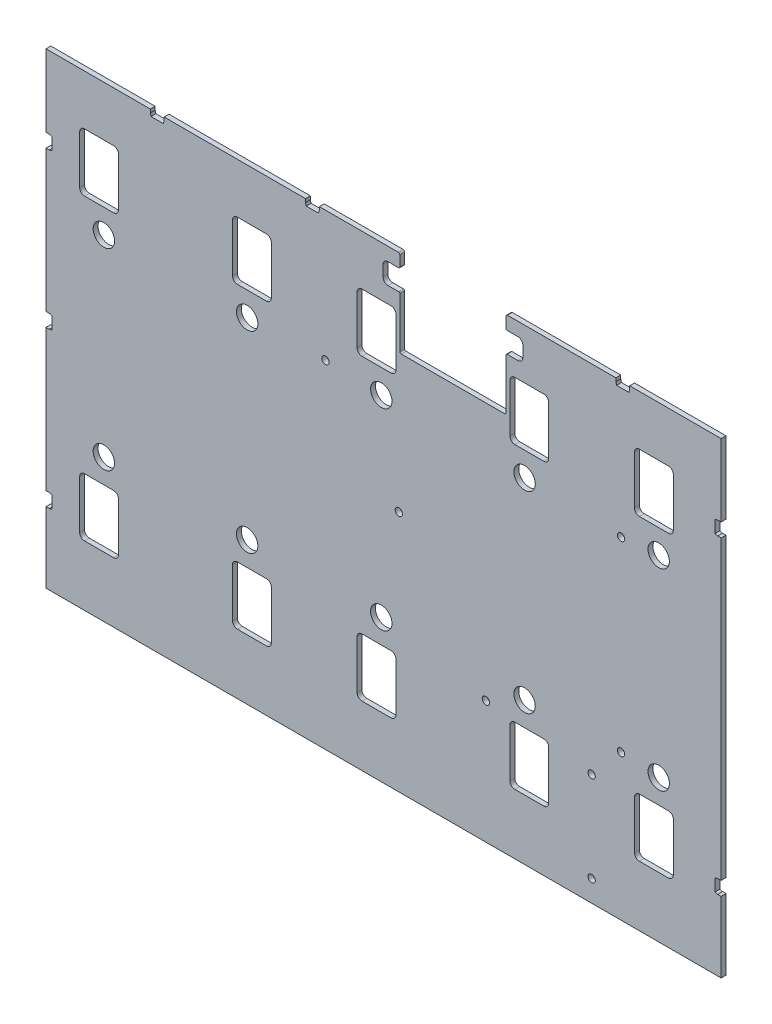
SolidWorks part; units mm, degrees
material "PP Film"
ref_plane "X-Y Datum" through (0, 0, 0) normal (0, 0, 1) x (1, 0, 0)
ref_plane "X-Z Datum" through (0, 0, 0) normal (0, 1, 0) x (1, 0, 0)
ref_plane "Y-Z Datum" through (0, 0, 0) normal (1, 0, 0) x (0, 0, -1)
sketch "Sketch1" plane through (0, 0, 0) normal (0, 0, 1) x (1, 0, 0)
  line L48 (-220.9897, 149.5877) -> (-220.9897, -156.2291)
  line L49 (-220.9897, -156.2291) -> (220.9897, -156.2291)
  line L50 (220.9897, -156.2291) -> (220.9897, 149.5877)
  line L51 (220.9897, 149.5877) -> (-220.9897, 149.5877)
extrude "Boss-Extrude1" add sketch "Sketch1" along normal blind 3.175 contours L50 L51 L48 L49 region at (0, -3.3207, 0)
sketch "Sketch2" plane through (0, 0, 3.175) normal (0, 0, 1) x (1, 0, 0)
  line L0 (-195.7605, 116.8) -> (-176.7105, 116.8) construction
  line L1 (-198.9355, 113.625) -> (-198.9355, 81.875) construction
  line L2 (-195.7605, 78.7) -> (-176.7105, 78.7) construction
  line L3 (-173.5355, 113.625) -> (-173.5355, 81.875) construction
  line L8 (-195.7605, 116.8) -> (-176.7105, 116.8)
  line L9 (-198.9355, 113.625) -> (-198.9355, 81.875)
  line L10 (-195.7605, 78.7) -> (-176.7105, 78.7)
  line L11 (-173.5355, 113.625) -> (-173.5355, 81.875)
  line L16 (-195.7605, -78.7) -> (-176.7105, -78.7) construction
  line L17 (-173.5355, -81.875) -> (-173.5355, -113.625) construction
  line L18 (-198.9355, -81.875) -> (-198.9355, -113.625) construction
  line L19 (-195.7605, -116.8) -> (-176.7105, -116.8) construction
  line L24 (-195.7605, -78.7) -> (-176.7105, -78.7)
  line L25 (-173.5355, -81.875) -> (-173.5355, -113.625)
  line L26 (-198.9355, -81.875) -> (-198.9355, -113.625)
  line L27 (-195.7605, -116.8) -> (-176.7105, -116.8)
  line L32 (-76.6655, -78.7) -> (-95.7155, -78.7) construction
  line L33 (-98.8905, -81.875) -> (-98.8905, -113.625) construction
  line L34 (-73.4905, -113.625) -> (-73.4905, -81.875) construction
  line L35 (-95.7155, -116.8) -> (-76.6655, -116.8) construction
  line L36 (-76.6655, -78.7) -> (-95.7155, -78.7)
  line L37 (-98.8905, -81.875) -> (-98.8905, -113.625)
  line L38 (-73.4905, -113.625) -> (-73.4905, -81.875)
  line L39 (-95.7155, -116.8) -> (-76.6655, -116.8)
  line L40 (-76.6655, 116.8) -> (-95.7155, 116.8) construction
  line L41 (-73.4905, 81.875) -> (-73.4905, 113.625) construction
  line L42 (-98.8905, 113.625) -> (-98.8905, 81.875) construction
  line L43 (-95.7155, 78.7) -> (-76.6655, 78.7) construction
  line L44 (-76.6655, 116.8) -> (-95.7155, 116.8)
  line L45 (-73.4905, 81.875) -> (-73.4905, 113.625)
  line L46 (-98.8905, 113.625) -> (-98.8905, 81.875)
  line L47 (-95.7155, 78.7) -> (-76.6655, 78.7)
  arc A0 (-173.5355, 113.625) -> (-176.7105, 116.8) centre (-176.7105, 113.625) ccw construction
  arc A1 (-195.7605, 116.8) -> (-198.9355, 113.625) centre (-195.7605, 113.625) ccw construction
  arc A2 (-198.9355, 81.875) -> (-195.7605, 78.7) centre (-195.7605, 81.875) ccw construction
  arc A3 (-176.7105, 78.7) -> (-173.5355, 81.875) centre (-176.7105, 81.875) ccw construction
  arc A8 (-173.5355, 113.625) -> (-176.7105, 116.8) centre (-176.7105, 113.625) ccw
  arc A9 (-195.7605, 116.8) -> (-198.9355, 113.625) centre (-195.7605, 113.625) ccw
  arc A10 (-198.9355, 81.875) -> (-195.7605, 78.7) centre (-195.7605, 81.875) ccw
  arc A11 (-176.7105, 78.7) -> (-173.5355, 81.875) centre (-176.7105, 81.875) ccw
  arc A16 (-195.7605, -78.7) -> (-198.9355, -81.875) centre (-195.7605, -81.875) ccw construction
  arc A17 (-173.5355, -81.875) -> (-176.7105, -78.7) centre (-176.7105, -81.875) ccw construction
  arc A18 (-176.7105, -116.8) -> (-173.5355, -113.625) centre (-176.7105, -113.625) ccw construction
  arc A19 (-198.9355, -113.625) -> (-195.7605, -116.8) centre (-195.7605, -113.625) ccw construction
  arc A24 (-195.7605, -78.7) -> (-198.9355, -81.875) centre (-195.7605, -81.875) ccw
  arc A25 (-173.5355, -81.875) -> (-176.7105, -78.7) centre (-176.7105, -81.875) ccw
  arc A26 (-176.7105, -116.8) -> (-173.5355, -113.625) centre (-176.7105, -113.625) ccw
  arc A27 (-198.9355, -113.625) -> (-195.7605, -116.8) centre (-195.7605, -113.625) ccw
  arc A32 (-73.4905, -81.875) -> (-76.6655, -78.7) centre (-76.6655, -81.875) ccw construction
  arc A33 (-95.7155, -78.7) -> (-98.8905, -81.875) centre (-95.7155, -81.875) ccw construction
  arc A34 (-76.6655, -116.8) -> (-73.4905, -113.625) centre (-76.6655, -113.625) ccw construction
  arc A35 (-98.8905, -113.625) -> (-95.7155, -116.8) centre (-95.7155, -113.625) ccw construction
  arc A36 (-73.4905, -81.875) -> (-76.6655, -78.7) centre (-76.6655, -81.875) ccw
  arc A37 (-95.7155, -78.7) -> (-98.8905, -81.875) centre (-95.7155, -81.875) ccw
  arc A38 (-76.6655, -116.8) -> (-73.4905, -113.625) centre (-76.6655, -113.625) ccw
  arc A39 (-98.8905, -113.625) -> (-95.7155, -116.8) centre (-95.7155, -113.625) ccw
  arc A40 (-73.4905, 113.625) -> (-76.6655, 116.8) centre (-76.6655, 113.625) ccw construction
  arc A41 (-95.7155, 116.8) -> (-98.8905, 113.625) centre (-95.7155, 113.625) ccw construction
  arc A42 (-76.6655, 78.7) -> (-73.4905, 81.875) centre (-76.6655, 81.875) ccw construction
  arc A43 (-98.8905, 81.875) -> (-95.7155, 78.7) centre (-95.7155, 81.875) ccw construction
  arc A44 (-73.4905, 113.625) -> (-76.6655, 116.8) centre (-76.6655, 113.625) ccw
  arc A45 (-95.7155, 116.8) -> (-98.8905, 113.625) centre (-95.7155, 113.625) ccw
  arc A46 (-76.6655, 78.7) -> (-73.4905, 81.875) centre (-76.6655, 81.875) ccw
  arc A47 (-98.8905, 81.875) -> (-95.7155, 78.7) centre (-95.7155, 81.875) ccw
extrude "Cut-Extrude1" cut sketch "Sketch2" against normal through all contours L26 A27 L27 A26 L25 A25 L24 A24 | L10 A11 L11 A8 L8 A9 L9 A10 region at (-186.2355, 97.75, 3.175) region at (-186.2355, -97.75, 3.175)
sketch "Sketch3" plane through (0, 0, 3.175) normal (0, 0, 1) x (1, 0, 0)
  line L5 (-176.7105, 116.8) -> (-195.7605, 116.8)
  line L6 (-173.5355, 81.875) -> (-173.5355, 113.625)
  line L7 (-195.7605, 78.7) -> (-176.7105, 78.7)
  line L13 (-198.9355, 113.625) -> (-198.9355, 81.875)
  line L14 (-176.7105, 116.8) -> (-195.7605, 116.8)
  line L15 (-173.5355, 81.875) -> (-173.5355, 113.625)
  line L21 (-195.7605, 78.7) -> (-176.7105, 78.7)
  line L22 (-198.9355, 113.625) -> (-198.9355, 81.875)
  line L23 (-173.5355, -113.625) -> (-173.5355, -81.875)
  line L29 (-195.7605, -116.8) -> (-176.7105, -116.8)
  line L30 (-198.9355, -81.875) -> (-198.9355, -113.625)
  line L31 (-176.7105, -78.7) -> (-195.7605, -78.7)
  line L36 (-173.5355, -113.625) -> (-173.5355, -81.875)
  line L37 (-195.7605, -116.8) -> (-176.7105, -116.8)
  line L38 (-198.9355, -81.875) -> (-198.9355, -113.625)
  line L39 (-176.7105, -78.7) -> (-195.7605, -78.7)
  line L40 (-76.6655, 116.8) -> (-95.7155, 116.8)
  line L41 (-98.8905, 113.625) -> (-98.8905, 81.875)
  line L42 (-95.7155, 78.7) -> (-76.6655, 78.7)
  line L43 (-73.4905, 81.875) -> (-73.4905, 113.625)
  line L44 (-76.6655, 116.8) -> (-95.7155, 116.8)
  line L45 (-98.8905, 113.625) -> (-98.8905, 81.875)
  line L46 (-95.7155, 78.7) -> (-76.6655, 78.7)
  line L47 (-73.4905, 81.875) -> (-73.4905, 113.625)
  line L48 (-95.7155, -116.8) -> (-76.6655, -116.8)
  line L49 (-98.8905, -81.875) -> (-98.8905, -113.625)
  line L50 (-76.6655, -78.7) -> (-95.7155, -78.7)
  line L51 (-73.4905, -113.625) -> (-73.4905, -81.875)
  line L52 (-95.7155, -116.8) -> (-76.6655, -116.8)
  line L53 (-98.8905, -81.875) -> (-98.8905, -113.625)
  line L54 (-76.6655, -78.7) -> (-95.7155, -78.7)
  line L55 (-73.4905, -113.625) -> (-73.4905, -81.875)
  arc A36 (-173.5355, 113.625) -> (-176.7105, 116.8) centre (-176.7105, 113.625) ccw
  arc A37 (-176.7105, 78.7) -> (-173.5355, 81.875) centre (-176.7105, 81.875) ccw
  arc A38 (-198.9355, 81.875) -> (-195.7605, 78.7) centre (-195.7605, 81.875) ccw
  arc A39 (-195.7605, 116.8) -> (-198.9355, 113.625) centre (-195.7605, 113.625) ccw
  arc A40 (-173.5355, 113.625) -> (-176.7105, 116.8) centre (-176.7105, 113.625) ccw
  arc A41 (-176.7105, 78.7) -> (-173.5355, 81.875) centre (-176.7105, 81.875) ccw
  arc A42 (-198.9355, 81.875) -> (-195.7605, 78.7) centre (-195.7605, 81.875) ccw
  arc A43 (-195.7605, 116.8) -> (-198.9355, 113.625) centre (-195.7605, 113.625) ccw
  arc A44 (-176.7105, -116.8) -> (-173.5355, -113.625) centre (-176.7105, -113.625) ccw
  arc A45 (-198.9355, -113.625) -> (-195.7605, -116.8) centre (-195.7605, -113.625) ccw
  arc A46 (-195.7605, -78.7) -> (-198.9355, -81.875) centre (-195.7605, -81.875) ccw
  arc A47 (-173.5355, -81.875) -> (-176.7105, -78.7) centre (-176.7105, -81.875) ccw
  arc A48 (-176.7105, -116.8) -> (-173.5355, -113.625) centre (-176.7105, -113.625) ccw
  arc A49 (-198.9355, -113.625) -> (-195.7605, -116.8) centre (-195.7605, -113.625) ccw
  arc A50 (-195.7605, -78.7) -> (-198.9355, -81.875) centre (-195.7605, -81.875) ccw
  arc A51 (-173.5355, -81.875) -> (-176.7105, -78.7) centre (-176.7105, -81.875) ccw
  arc A52 (-95.7155, 116.8) -> (-98.8905, 113.625) centre (-95.7155, 113.625) ccw
  arc A53 (-98.8905, 81.875) -> (-95.7155, 78.7) centre (-95.7155, 81.875) ccw
  arc A54 (-76.6655, 78.7) -> (-73.4905, 81.875) centre (-76.6655, 81.875) ccw
  arc A55 (-73.4905, 113.625) -> (-76.6655, 116.8) centre (-76.6655, 113.625) ccw
  arc A56 (-95.7155, 116.8) -> (-98.8905, 113.625) centre (-95.7155, 113.625) ccw
  arc A57 (-98.8905, 81.875) -> (-95.7155, 78.7) centre (-95.7155, 81.875) ccw
  arc A58 (-76.6655, 78.7) -> (-73.4905, 81.875) centre (-76.6655, 81.875) ccw
  arc A59 (-73.4905, 113.625) -> (-76.6655, 116.8) centre (-76.6655, 113.625) ccw
  arc A60 (-76.6655, -116.8) -> (-73.4905, -113.625) centre (-76.6655, -113.625) ccw
  arc A61 (-98.8905, -113.625) -> (-95.7155, -116.8) centre (-95.7155, -113.625) ccw
  arc A62 (-95.7155, -78.7) -> (-98.8905, -81.875) centre (-95.7155, -81.875) ccw
  arc A63 (-73.4905, -81.875) -> (-76.6655, -78.7) centre (-76.6655, -81.875) ccw
  arc A64 (-76.6655, -116.8) -> (-73.4905, -113.625) centre (-76.6655, -113.625) ccw
  arc A65 (-98.8905, -113.625) -> (-95.7155, -116.8) centre (-95.7155, -113.625) ccw
  arc A66 (-95.7155, -78.7) -> (-98.8905, -81.875) centre (-95.7155, -81.875) ccw
  arc A67 (-73.4905, -81.875) -> (-76.6655, -78.7) centre (-76.6655, -81.875) ccw
  dimension "D1" = 0
  dimension "D2" = 0
  dimension "D3" = 0
  dimension "D4" = 0
extrude "Cut-Extrude2" cut sketch "Sketch3" against normal through all contours L55 A67 L54 A66 L53 A65 L52 A64 | L47 A59 L44 A56 L45 A57 L46 A58 region at (-86.1905, 97.75, 3.175) region at (-86.1905, -97.75, 3.175)
pattern_linear "LPattern1" count 3 spacing 181.614 along (1, 0, 0) of "Cut-Extrude1"
pattern_linear "LPattern2" count 2 spacing 181.614 along (1, 0, 0) of "Cut-Extrude2"
sketch "Sketch4" plane through (0, 0, 3.175) normal (0, 0, 1) x (1, 0, 0)
  line L0 (78.901, 149.0877) -> (75.901, 149.0877) construction
  line L1 (75.901, 149.0877) -> (75.901, 94.0877) construction
  line L2 (75.901, 94.0877) -> (78.901, 94.0877) construction
  line L3 (78.901, 94.0877) -> (78.901, 149.0877) construction
  line L4 (9.901, 139.5877) -> (2.901, 139.5877)
  line L5 (0.901, 137.5877) -> (0.901, 130.5877)
  line L6 (2.901, 128.5877) -> (9.901, 128.5877)
  line L7 (11.901, 126.5877) -> (11.901, 141.5877)
  line L8 (9.901, 139.5877) -> (2.901, 139.5877) construction
  line L9 (0.901, 137.5877) -> (0.901, 130.5877) construction
  line L10 (2.901, 128.5877) -> (9.901, 128.5877) construction
  line L11 (11.901, 126.5877) -> (11.901, 141.5877) construction
  line L12 (89.901, 130.5877) -> (89.901, 137.5877)
  line L13 (87.901, 139.5877) -> (80.901, 139.5877)
  line L14 (78.901, 141.5877) -> (78.901, 126.5877)
  line L15 (80.901, 128.5877) -> (87.901, 128.5877)
  line L16 (89.901, 130.5877) -> (89.901, 137.5877) construction
  line L17 (87.901, 139.5877) -> (80.901, 139.5877) construction
  line L18 (78.901, 141.5877) -> (78.901, 126.5877) construction
  line L19 (80.901, 128.5877) -> (87.901, 128.5877) construction
  line L20 (11.901, 94.0877) -> (14.901, 94.0877) construction
  line L21 (14.901, 94.0877) -> (14.901, 149.0877) construction
  line L23 (11.901, 149.0877) -> (11.901, 94.0877) construction
  line L24 (78.901, 149.0877) -> (75.901, 149.0877) construction
  line L25 (75.901, 149.0877) -> (75.901, 94.0877) construction
  line L26 (75.901, 94.0877) -> (78.901, 94.0877) construction
  line L27 (78.901, 94.0877) -> (78.901, 149.0877) construction
  line L28 (11.901, 94.0877) -> (14.901, 94.0877) construction
  line L29 (14.901, 94.0877) -> (14.901, 149.0877) construction
  line L31 (11.901, 149.0877) -> (11.901, 94.0877) construction
  line L32 (14.901, 94.0877) -> (75.901, 94.0877) construction
  line L33 (11.901, 149.0877) -> (11.901, 149.5877) construction
  line L34 (220.9897, 149.5877) -> (-220.9897, 149.5877) construction
  line L35 (78.901, 149.0877) -> (78.901, 149.5877) construction
  line L36 (220.9897, 149.5877) -> (-220.9897, 149.5877) construction
  line L37 (220.9897, 149.5877) -> (-220.9897, 149.5877) construction
  line L38 (9.901, 140.8577) -> (2.901, 140.8577)
  line L39 (-0.369, 137.5877) -> (-0.369, 130.5877)
  line L40 (2.901, 127.3177) -> (9.901, 127.3177)
  line L41 (10.631, 149.5877) -> (10.631, 92.8177)
  line L42 (10.631, 92.8177) -> (14.901, 92.8177)
  line L43 (14.901, 92.8177) -> (75.901, 92.8177)
  line L44 (75.901, 92.8177) -> (80.171, 92.8177)
  line L45 (80.171, 92.8177) -> (80.171, 149.5877)
  line L46 (80.171, 127.3177) -> (87.901, 127.3177)
  line L47 (91.171, 130.5877) -> (91.171, 137.5877)
  line L48 (87.901, 140.8577) -> (80.171, 140.8577)
  line L49 (10.631, 149.0877) -> (10.631, 92.8177) construction
  line L50 (80.171, 92.8177) -> (80.171, 149.0877) construction
  line L51 (87.901, 140.8577) -> (80.901, 140.8577) construction
  line L52 (80.901, 127.3177) -> (87.901, 127.3177) construction
  line L53 (10.631, 149.5877) -> (80.171, 149.5877)
  arc A0 (9.901, 140.8577) -> (10.631, 141.5877) centre (9.901, 141.5877) ccw
  arc A1 (2.901, 140.8577) -> (-0.369, 137.5877) centre (2.901, 137.5877) ccw
  arc A2 (-0.369, 130.5877) -> (2.901, 127.3177) centre (2.901, 130.5877) ccw
  arc A3 (10.631, 126.5877) -> (9.901, 127.3177) centre (9.901, 126.5877) ccw
  arc A4 (2.901, 139.5877) -> (0.901, 137.5877) centre (2.901, 137.5877) ccw
  arc A5 (0.901, 130.5877) -> (2.901, 128.5877) centre (2.901, 130.5877) ccw
  arc A6 (11.901, 126.5877) -> (9.901, 128.5877) centre (9.901, 126.5877) ccw
  arc A7 (9.901, 139.5877) -> (11.901, 141.5877) centre (9.901, 141.5877) ccw
  arc A8 (2.901, 139.5877) -> (0.901, 137.5877) centre (2.901, 137.5877) ccw construction
  arc A9 (0.901, 130.5877) -> (2.901, 128.5877) centre (2.901, 130.5877) ccw construction
  arc A10 (11.901, 126.5877) -> (9.901, 128.5877) centre (9.901, 126.5877) ccw construction
  arc A11 (9.901, 139.5877) -> (11.901, 141.5877) centre (9.901, 141.5877) ccw construction
  arc A12 (89.901, 137.5877) -> (87.901, 139.5877) centre (87.901, 137.5877) ccw
  arc A13 (78.901, 141.5877) -> (80.901, 139.5877) centre (80.901, 141.5877) ccw
  arc A14 (80.901, 128.5877) -> (78.901, 126.5877) centre (80.901, 126.5877) ccw
  arc A15 (87.901, 128.5877) -> (89.901, 130.5877) centre (87.901, 130.5877) ccw
  arc A16 (89.901, 137.5877) -> (87.901, 139.5877) centre (87.901, 137.5877) ccw construction
  arc A17 (78.901, 141.5877) -> (80.901, 139.5877) centre (80.901, 141.5877) ccw construction
  arc A18 (80.901, 128.5877) -> (78.901, 126.5877) centre (80.901, 126.5877) ccw construction
  arc A19 (87.901, 128.5877) -> (89.901, 130.5877) centre (87.901, 130.5877) ccw construction
  arc A20 (87.901, 127.3177) -> (91.171, 130.5877) centre (87.901, 130.5877) ccw
  arc A21 (91.171, 137.5877) -> (87.901, 140.8577) centre (87.901, 137.5877) ccw
  arc A22 (80.171, 141.5877) -> (80.901, 140.8577) centre (80.901, 141.5877) ccw
  arc A23 (80.901, 127.3177) -> (80.171, 126.5877) centre (80.901, 126.5877) ccw
  dimension "D1" = 0
  dimension "D2" = 0
  dimension "D3" = 1.27
  dimension "D4" = 1.27
extrude "Cut-Extrude3" cut sketch "Sketch4" against normal through all contours L35 L37 L33 L29 L32 L25 L24 | L31 L11 L28 L29 | A11 L8 A8 L9 A9 L10 A10 L11 | L26 L27 L18 L24 L25 | L19 A19 L16 A16 L17 A17 L18 A18 | L53 L41 L42 L43 L44 L45 | A3 L41 A0 L38 A1 L39 A2 L40 | L47 A21 L48 L45 L46 A20 | A23 L46 L45 | A22 L45 L48 region at (6.401, 139.7737, 3.175) region at (45.401, 121.0999, 3.175) region at (80.3341, 141.0208, 3.175) region at (80.536, 140.6833, 3.175) region at (80.3341, 127.1547, 3.175) body kept at (220.9897, 149.5877, 0)
sketch "Sketch5" plane through (0, 0, 3.175) normal (0, 0, 1) x (1, 0, 0)
  circle A20 centre (-183.1177, 63.0089) radius 7 construction
  circle A21 centre (-183.1177, -63.0089) radius 7 construction
  circle A22 centre (-183.1177, 63.0089) radius 7
  circle A23 centre (-183.1177, -63.0089) radius 7
  circle A24 centre (-89.3083, -63.0089) radius 7 construction
  circle A25 centre (-89.3083, -63.0089) radius 7
  circle A26 centre (-89.3083, 63.0089) radius 7 construction
  circle A27 centre (-89.3083, 63.0089) radius 7
  circle A28 centre (180.1103, -63.0089) radius 7 construction
  circle A29 centre (180.1103, 63.0089) radius 7 construction
  circle A30 centre (92.3057, 63.0089) radius 7 construction
  circle A31 centre (92.3057, -63.0089) radius 7 construction
  circle A32 centre (-1.5037, -63.0089) radius 7 construction
  circle A33 centre (-1.5037, 63.0089) radius 7 construction
  circle A34 centre (180.1103, -63.0089) radius 7
  circle A35 centre (180.1103, 63.0089) radius 7
  circle A36 centre (92.3057, 63.0089) radius 7
  circle A37 centre (92.3057, -63.0089) radius 7
  circle A38 centre (-1.5037, -63.0089) radius 7
  circle A39 centre (-1.5037, 63.0089) radius 7
extrude "Cut-Extrude4" cut sketch "Sketch5" against normal through all
sketch "Sketch6" plane through (0, 0, 3.175) normal (0, 0, 1) x (1, 0, 0)
  point P0 (0, 0)
  point P3 (-38.0103, 64.5)
  point P5 (9.9897, 2.5)
  point P7 (66.9897, -76)
  point P9 (136.208, -142.216)
  point P11 (136.208, -83.216)
  point P13 (155.4897, -61)
  point P15 (155.4897, 61)
  point P17 (0, 0)
hole_wizard "M4 Clearance Hole1" positions "Sketch6" profile "Sketch7" hole size "M4" standard "ANSI Metric" end condition through all
sketch "Sketch7" plane through (-38.0103, 64.5, 3.175) normal (1, 0, 0) x (0, -1, 0)
  line L0 (0, 0) -> (0, 3.175)
  line L1 (0, 3.175) -> (2.4, 3.175)
  line L2 (2.4, 3.175) -> (2.4, 0)
  line L5 (2.4, 0) -> (0, 0)
  line L11 (0, -6.35) -> (0, 107.95) construction
  dimension "Thru Hole Dia." = 4.8
  dimension "Thru Hole Depth" = 3.175
fillet "Fillet1" radius 1 4 edges at (10.631, 92.8177, 1.5875) (80.171, 92.8177, 1.5875) (80.171, 149.5877, 1.5875) (10.631, 149.5877, 1.5875)
sketch "Sketch8" plane through (0, 0, 3.175) normal (0, 0, 1) x (1, 0, 0)
  line L0 (222.7547, 94.2531) -> (222.7547, 94.1133)
  line L1 (222.7547, 94.2531) -> (222.7547, 94.1133) construction
  line L2 (222.7547, 94.1133) -> (222.7547, 93.9266)
  line L3 (222.7547, 94.1133) -> (222.7547, 93.9266) construction
  line L4 (222.7547, 93.9266) -> (222.7547, 93.6505)
  line L5 (222.7547, 93.9266) -> (222.7547, 93.6505) construction
  line L6 (222.7547, 93.6505) -> (222.7547, 93.5265)
  line L7 (222.7547, 93.6505) -> (222.7547, 93.5265) construction
  line L8 (222.7547, 93.5265) -> (221.9897, 93.5265)
  line L9 (222.7547, 93.5265) -> (221.9897, 93.5265) construction
  line L10 (221.9897, 93.5265) -> (221.9897, 93.6505)
  line L11 (221.9897, 93.5265) -> (221.9897, 93.6505) construction
  line L12 (221.9897, 93.6505) -> (221.9897, 93.9328)
  line L13 (221.9897, 93.6505) -> (221.9897, 93.9328) construction
  line L14 (221.9897, 93.9328) -> (221.9897, 94.1133)
  line L15 (221.9897, 93.9328) -> (221.9897, 94.1133) construction
  line L16 (221.9897, 94.1133) -> (221.9897, 94.166)
  line L17 (221.9897, 94.1133) -> (221.9897, 94.166) construction
  line L18 (221.8897, 94.266) -> (218.8697, 94.266)
  line L19 (221.8897, 94.266) -> (218.8697, 94.266) construction
  line L20 (218.8697, 94.266) -> (217.9897, 94.5017)
  line L21 (218.8697, 94.266) -> (217.9897, 94.5017) construction
  line L22 (217.9897, 94.5017) -> (217.9897, 101.0402)
  line L23 (217.9897, 94.5017) -> (217.9897, 101.0402) construction
  line L24 (217.9897, 101.0402) -> (218.8697, 101.276)
  line L25 (217.9897, 101.0402) -> (218.8697, 101.276) construction
  line L26 (218.8697, 101.276) -> (221.8897, 101.276)
  line L27 (218.8697, 101.276) -> (221.8897, 101.276) construction
  line L28 (221.9897, 101.376) -> (221.9897, 101.4286)
  line L29 (221.9897, 101.376) -> (221.9897, 101.4286) construction
  line L30 (221.9897, 101.4286) -> (221.9897, 101.5441)
  line L31 (221.9897, 101.4286) -> (221.9897, 101.5441) construction
  line L32 (221.9897, 101.5441) -> (221.9897, 101.7755)
  line L33 (221.9897, 101.5441) -> (221.9897, 101.7755) construction
  line L34 (221.9897, 101.7755) -> (221.9897, 101.9762)
  line L35 (221.9897, 101.7755) -> (221.9897, 101.9762) construction
  line L36 (221.9897, 101.9762) -> (221.9897, 102.0154)
  line L37 (221.9897, 101.9762) -> (221.9897, 102.0154) construction
  line L38 (221.9897, 102.0154) -> (222.7547, 102.0154)
  line L39 (221.9897, 102.0154) -> (222.7547, 102.0154) construction
  line L40 (222.7547, 102.0154) -> (222.7547, 101.9762)
  line L41 (222.7547, 102.0154) -> (222.7547, 101.9762) construction
  line L42 (222.7547, 101.9762) -> (222.7547, 101.7755)
  line L43 (222.7547, 101.9762) -> (222.7547, 101.7755) construction
  line L44 (222.7547, 101.7755) -> (222.7547, 101.5441)
  line L45 (222.7547, 101.7755) -> (222.7547, 101.5441) construction
  line L46 (222.7547, 101.5441) -> (222.7547, 101.4208)
  line L47 (222.7547, 101.5441) -> (222.7547, 101.4208) construction
  line L48 (222.7547, 101.4208) -> (222.7547, 101.2888)
  line L49 (222.7547, 101.4208) -> (222.7547, 101.2888) construction
  line L50 (222.7547, 101.2888) -> (222.7547, 101.2285)
  line L51 (222.7547, 101.2888) -> (222.7547, 101.2285) construction
  line L52 (222.8547, 101.1285) -> (223.0372, 101.1285)
  line L53 (222.8547, 101.1285) -> (223.0372, 101.1285) construction
  line L54 (223.1372, 101.2272) -> (223.1372, 101.411)
  line L55 (223.1372, 101.2272) -> (223.1372, 101.411) construction
  line L56 (223.2372, 101.511) -> (223.4197, 101.511)
  line L57 (223.2372, 101.511) -> (223.4197, 101.511) construction
  line L58 (223.5197, 101.411) -> (223.5197, 94.131)
  line L59 (223.5197, 101.411) -> (223.5197, 94.131) construction
  line L60 (223.4197, 94.031) -> (223.2372, 94.031)
  line L61 (223.4197, 94.031) -> (223.2372, 94.031) construction
  line L62 (223.1372, 94.131) -> (223.1372, 94.3135)
  line L63 (223.1372, 94.131) -> (223.1372, 94.3135) construction
  line L64 (223.0372, 94.4135) -> (222.8547, 94.4135)
  line L65 (223.0372, 94.4135) -> (222.8547, 94.4135) construction
  line L66 (222.7547, 94.3137) -> (222.7547, 94.2531)
  line L67 (222.7547, 94.3137) -> (222.7547, 94.2531) construction
  line L68 (-223.1372, 94.3147) -> (-223.1372, 94.131)
  line L69 (-223.1372, 94.3147) -> (-223.1372, 94.131) construction
  line L70 (-223.2372, 94.031) -> (-223.4197, 94.031)
  line L71 (-223.2372, 94.031) -> (-223.4197, 94.031) construction
  line L72 (-223.5197, 94.131) -> (-223.5197, 101.411)
  line L73 (-223.5197, 94.131) -> (-223.5197, 101.411) construction
  line L74 (-223.4197, 101.511) -> (-223.2372, 101.511)
  line L75 (-223.4197, 101.511) -> (-223.2372, 101.511) construction
  line L76 (-223.1372, 101.411) -> (-223.1372, 101.2285)
  line L77 (-223.1372, 101.411) -> (-223.1372, 101.2285) construction
  line L78 (-223.0372, 101.1285) -> (-222.8547, 101.1285)
  line L79 (-223.0372, 101.1285) -> (-222.8547, 101.1285) construction
  line L80 (-222.7547, 101.2282) -> (-222.7547, 101.2888)
  line L81 (-222.7547, 101.2282) -> (-222.7547, 101.2888) construction
  line L82 (-222.7547, 101.2888) -> (-222.7547, 101.4286)
  line L83 (-222.7547, 101.2888) -> (-222.7547, 101.4286) construction
  line L84 (-222.7547, 101.4286) -> (-222.7547, 101.5441)
  line L85 (-222.7547, 101.4286) -> (-222.7547, 101.5441) construction
  line L86 (-222.7547, 101.5441) -> (-222.7547, 101.7755)
  line L87 (-222.7547, 101.5441) -> (-222.7547, 101.7755) construction
  line L88 (-222.7547, 101.7755) -> (-222.7547, 101.9762)
  line L89 (-222.7547, 101.7755) -> (-222.7547, 101.9762) construction
  line L90 (-222.7547, 101.9762) -> (-222.7547, 102.0154)
  line L91 (-222.7547, 101.9762) -> (-222.7547, 102.0154) construction
  line L92 (-222.7547, 102.0154) -> (-221.9897, 102.0154)
  line L93 (-222.7547, 102.0154) -> (-221.9897, 102.0154) construction
  line L94 (-221.9897, 102.0154) -> (-221.9897, 101.9762)
  line L95 (-221.9897, 102.0154) -> (-221.9897, 101.9762) construction
  line L96 (-221.9897, 101.9762) -> (-221.9897, 101.7755)
  line L97 (-221.9897, 101.9762) -> (-221.9897, 101.7755) construction
  line L98 (-221.9897, 101.7755) -> (-221.9897, 101.5441)
  line L99 (-221.9897, 101.7755) -> (-221.9897, 101.5441) construction
  line L100 (-221.9897, 101.5441) -> (-221.9897, 101.4208)
  line L101 (-221.9897, 101.5441) -> (-221.9897, 101.4208) construction
  line L102 (-221.9897, 101.4208) -> (-221.9897, 101.376)
  line L103 (-221.9897, 101.4208) -> (-221.9897, 101.376) construction
  line L104 (-221.8897, 101.276) -> (-218.8697, 101.276)
  line L105 (-221.8897, 101.276) -> (-218.8697, 101.276) construction
  line L106 (-218.8697, 101.276) -> (-217.9897, 101.0402)
  line L107 (-218.8697, 101.276) -> (-217.9897, 101.0402) construction
  line L108 (-217.9897, 101.0402) -> (-217.9897, 94.5017)
  line L109 (-217.9897, 101.0402) -> (-217.9897, 94.5017) construction
  line L110 (-217.9897, 94.5017) -> (-218.8697, 94.266)
  line L111 (-217.9897, 94.5017) -> (-218.8697, 94.266) construction
  line L112 (-218.8697, 94.266) -> (-221.8897, 94.266)
  line L113 (-218.8697, 94.266) -> (-221.8897, 94.266) construction
  line L114 (-221.9897, 94.166) -> (-221.9897, 94.1133)
  line L115 (-221.9897, 94.166) -> (-221.9897, 94.1133) construction
  line L116 (-221.9897, 94.1133) -> (-221.9897, 93.9266)
  line L117 (-221.9897, 94.1133) -> (-221.9897, 93.9266) construction
  line L118 (-221.9897, 93.9266) -> (-221.9897, 93.6505)
  line L119 (-221.9897, 93.9266) -> (-221.9897, 93.6505) construction
  line L120 (-221.9897, 93.6505) -> (-221.9897, 93.5265)
  line L121 (-221.9897, 93.6505) -> (-221.9897, 93.5265) construction
  line L122 (-221.9897, 93.5265) -> (-222.7547, 93.5265)
  line L123 (-221.9897, 93.5265) -> (-222.7547, 93.5265) construction
  line L124 (-222.7547, 93.5265) -> (-222.7547, 93.6505)
  line L125 (-222.7547, 93.5265) -> (-222.7547, 93.6505) construction
  line L126 (-222.7547, 93.6505) -> (-222.7547, 93.9328)
  line L127 (-222.7547, 93.6505) -> (-222.7547, 93.9328) construction
  line L128 (-222.7547, 93.9328) -> (-222.7547, 94.1133)
  line L129 (-222.7547, 93.9328) -> (-222.7547, 94.1133) construction
  line L130 (-222.7547, 94.1133) -> (-222.7547, 94.2531)
  line L131 (-222.7547, 94.1133) -> (-222.7547, 94.2531) construction
  line L132 (-222.7547, 94.2531) -> (-222.7547, 94.3135)
  line L133 (-222.7547, 94.2531) -> (-222.7547, 94.3135) construction
  line L134 (-222.8547, 94.4135) -> (-223.0372, 94.4135)
  line L135 (-222.8547, 94.4135) -> (-223.0372, 94.4135) construction
  line L136 (223.1372, -101.9719) -> (223.1372, -101.7891)
  line L137 (223.1372, -101.9719) -> (223.1372, -101.7891) construction
  line L138 (223.2372, -101.6891) -> (223.4197, -101.6891)
  line L139 (223.2372, -101.6891) -> (223.4197, -101.6891) construction
  line L140 (223.5197, -101.7891) -> (223.5197, -109.0691)
  line L141 (223.5197, -101.7891) -> (223.5197, -109.0691) construction
  line L142 (223.4197, -109.1691) -> (223.2372, -109.1691)
  line L143 (223.4197, -109.1691) -> (223.2372, -109.1691) construction
  line L144 (223.1372, -109.0691) -> (223.1372, -108.8866)
  line L145 (223.1372, -109.0691) -> (223.1372, -108.8866) construction
  line L146 (223.0372, -108.7866) -> (222.8547, -108.7866)
  line L147 (223.0372, -108.7866) -> (222.8547, -108.7866) construction
  line L148 (222.7547, -108.8856) -> (222.7547, -109.0218)
  line L149 (222.7547, -108.8856) -> (222.7547, -109.0218) construction
  line L150 (222.7547, -109.0218) -> (222.7547, -109.1786)
  line L151 (222.7547, -109.0218) -> (222.7547, -109.1786) construction
  line L152 (222.7547, -109.1786) -> (222.7547, -109.2425)
  line L153 (222.7547, -109.1786) -> (222.7547, -109.2425) construction
  line L154 (222.7547, -109.2425) -> (222.7547, -109.4969)
  line L155 (222.7547, -109.2425) -> (222.7547, -109.4969) construction
  line L156 (222.7547, -109.4969) -> (222.7547, -109.6589)
  line L157 (222.7547, -109.4969) -> (222.7547, -109.6589) construction
  line L158 (222.7547, -109.6589) -> (221.9897, -109.6589)
  line L159 (222.7547, -109.6589) -> (221.9897, -109.6589) construction
  line L160 (221.9897, -109.6589) -> (221.9897, -109.4969)
  line L161 (221.9897, -109.6589) -> (221.9897, -109.4969) construction
  line L162 (221.9897, -109.4969) -> (221.9897, -109.2415)
  line L163 (221.9897, -109.4969) -> (221.9897, -109.2415) construction
  line L164 (221.9897, -109.2415) -> (221.9897, -109.1786)
  line L165 (221.9897, -109.2415) -> (221.9897, -109.1786) construction
  line L166 (221.9897, -109.1786) -> (221.9897, -109.0341)
  line L167 (221.9897, -109.1786) -> (221.9897, -109.0341) construction
  line L168 (221.8897, -108.9341) -> (218.8697, -108.9341)
  line L169 (221.8897, -108.9341) -> (218.8697, -108.9341) construction
  line L170 (218.8697, -108.9341) -> (217.9897, -108.6983)
  line L171 (218.8697, -108.9341) -> (217.9897, -108.6983) construction
  line L172 (217.9897, -108.6983) -> (217.9897, -102.1598)
  line L173 (217.9897, -108.6983) -> (217.9897, -102.1598) construction
  line L174 (217.9897, -102.1598) -> (218.8697, -101.9241)
  line L175 (217.9897, -102.1598) -> (218.8697, -101.9241) construction
  line L176 (218.8697, -101.9241) -> (221.8897, -101.9241)
  line L177 (218.8697, -101.9241) -> (221.8897, -101.9241) construction
  line L178 (221.9897, -101.8243) -> (221.9897, -101.6823)
  line L179 (221.9897, -101.8243) -> (221.9897, -101.6823) construction
  line L180 (221.9897, -101.6823) -> (221.9897, -101.6166)
  line L181 (221.9897, -101.6823) -> (221.9897, -101.6166) construction
  line L182 (221.9897, -101.6166) -> (221.9897, -101.3629)
  line L183 (221.9897, -101.6166) -> (221.9897, -101.3629) construction
  line L184 (221.9897, -101.3629) -> (221.9897, -101.1992)
  line L185 (221.9897, -101.3629) -> (221.9897, -101.1992) construction
  line L186 (221.9897, -101.1992) -> (222.7547, -101.1992)
  line L187 (221.9897, -101.1992) -> (222.7547, -101.1992) construction
  line L188 (222.7547, -101.1992) -> (222.7547, -101.3629)
  line L189 (222.7547, -101.1992) -> (222.7547, -101.3629) construction
  line L190 (222.7547, -101.3629) -> (222.7547, -101.6166)
  line L191 (222.7547, -101.3629) -> (222.7547, -101.6166) construction
  line L192 (222.7547, -101.6166) -> (222.7547, -101.6823)
  line L193 (222.7547, -101.6166) -> (222.7547, -101.6823) construction
  line L194 (222.7547, -101.6823) -> (222.7547, -101.8383)
  line L195 (222.7547, -101.6823) -> (222.7547, -101.8383) construction
  line L196 (222.7547, -101.8383) -> (222.7547, -101.9716)
  line L197 (222.7547, -101.8383) -> (222.7547, -101.9716) construction
  line L198 (222.8547, -102.0716) -> (223.0372, -102.0716)
  line L199 (222.8547, -102.0716) -> (223.0372, -102.0716) construction
  line L200 (-222.7547, -0.2383) -> (-222.7547, -0.0823)
  line L201 (-222.7547, -0.2383) -> (-222.7547, -0.0823) construction
  line L202 (-222.7547, -0.0823) -> (-222.7547, -0.0166)
  line L203 (-222.7547, -0.0823) -> (-222.7547, -0.0166) construction
  line L204 (-222.7547, -0.0166) -> (-222.7547, 0.2371)
  line L205 (-222.7547, -0.0166) -> (-222.7547, 0.2371) construction
  line L206 (-222.7547, 0.2371) -> (-222.7547, 0.4008)
  line L207 (-222.7547, 0.2371) -> (-222.7547, 0.4008) construction
  line L208 (-222.7547, 0.4008) -> (-221.9897, 0.4008)
  line L209 (-222.7547, 0.4008) -> (-221.9897, 0.4008) construction
  line L210 (-221.9897, 0.4008) -> (-221.9897, 0.2371)
  line L211 (-221.9897, 0.4008) -> (-221.9897, 0.2371) construction
  line L212 (-221.9897, 0.2371) -> (-221.9897, -0.0166)
  line L213 (-221.9897, 0.2371) -> (-221.9897, -0.0166) construction
  line L214 (-221.9897, -0.0166) -> (-221.9897, -0.0823)
  line L215 (-221.9897, -0.0166) -> (-221.9897, -0.0823) construction
  line L216 (-221.9897, -0.0823) -> (-221.9897, -0.2241)
  line L217 (-221.9897, -0.0823) -> (-221.9897, -0.2241) construction
  line L218 (-221.8897, -0.3241) -> (-218.8697, -0.3241)
  line L219 (-221.8897, -0.3241) -> (-218.8697, -0.3241) construction
  line L220 (-218.8697, -0.3241) -> (-217.9897, -0.5598)
  line L221 (-218.8697, -0.3241) -> (-217.9897, -0.5598) construction
  line L222 (-217.9897, -0.5598) -> (-217.9897, -7.0983)
  line L223 (-217.9897, -0.5598) -> (-217.9897, -7.0983) construction
  line L224 (-217.9897, -7.0983) -> (-218.8697, -7.3341)
  line L225 (-217.9897, -7.0983) -> (-218.8697, -7.3341) construction
  line L226 (-218.8697, -7.3341) -> (-221.8897, -7.3341)
  line L227 (-218.8697, -7.3341) -> (-221.8897, -7.3341) construction
  line L228 (-221.9897, -7.4338) -> (-221.9897, -7.5786)
  line L229 (-221.9897, -7.4338) -> (-221.9897, -7.5786) construction
  line L230 (-221.9897, -7.5786) -> (-221.9897, -7.6425)
  line L231 (-221.9897, -7.5786) -> (-221.9897, -7.6425) construction
  line L232 (-221.9897, -7.6425) -> (-221.9897, -7.8969)
  line L233 (-221.9897, -7.6425) -> (-221.9897, -7.8969) construction
  line L234 (-221.9897, -7.8969) -> (-221.9897, -8.0589)
  line L235 (-221.9897, -7.8969) -> (-221.9897, -8.0589) construction
  line L236 (-221.9897, -8.0589) -> (-222.7547, -8.0589)
  line L237 (-221.9897, -8.0589) -> (-222.7547, -8.0589) construction
  line L238 (-222.7547, -8.0589) -> (-222.7547, -7.8969)
  line L239 (-222.7547, -8.0589) -> (-222.7547, -7.8969) construction
  line L240 (-222.7547, -7.8969) -> (-222.7547, -7.6415)
  line L241 (-222.7547, -7.8969) -> (-222.7547, -7.6415) construction
  line L242 (-222.7547, -7.6415) -> (-222.7547, -7.5786)
  line L243 (-222.7547, -7.6415) -> (-222.7547, -7.5786) construction
  line L244 (-222.7547, -7.5786) -> (-222.7547, -7.4198)
  line L245 (-222.7547, -7.5786) -> (-222.7547, -7.4198) construction
  line L246 (-222.7547, -7.4198) -> (-222.7547, -7.2866)
  line L247 (-222.7547, -7.4198) -> (-222.7547, -7.2866) construction
  line L248 (-222.8547, -7.1866) -> (-223.0372, -7.1866)
  line L249 (-222.8547, -7.1866) -> (-223.0372, -7.1866) construction
  line L250 (-223.1372, -7.2862) -> (-223.1372, -7.4691)
  line L251 (-223.1372, -7.2862) -> (-223.1372, -7.4691) construction
  line L252 (-223.2372, -7.5691) -> (-223.4197, -7.5691)
  line L253 (-223.2372, -7.5691) -> (-223.4197, -7.5691) construction
  line L254 (-223.5197, -7.4691) -> (-223.5197, -0.1891)
  line L255 (-223.5197, -7.4691) -> (-223.5197, -0.1891) construction
  line L256 (-223.4197, -0.0891) -> (-223.2372, -0.0891)
  line L257 (-223.4197, -0.0891) -> (-223.2372, -0.0891) construction
  line L258 (-223.1372, -0.1891) -> (-223.1372, -0.3716)
  line L259 (-223.1372, -0.1891) -> (-223.1372, -0.3716) construction
  line L260 (-223.0372, -0.4716) -> (-222.8547, -0.4716)
  line L261 (-223.0372, -0.4716) -> (-222.8547, -0.4716) construction
  line L262 (-222.7547, -0.3725) -> (-222.7547, -0.2383)
  line L263 (-222.7547, -0.3725) -> (-222.7547, -0.2383) construction
  line L264 (-222.7547, -101.8383) -> (-222.7547, -101.6823)
  line L265 (-222.7547, -101.8383) -> (-222.7547, -101.6823) construction
  line L266 (-222.7547, -101.6823) -> (-222.7547, -101.6166)
  line L267 (-222.7547, -101.6823) -> (-222.7547, -101.6166) construction
  line L268 (-222.7547, -101.6166) -> (-222.7547, -101.3629)
  line L269 (-222.7547, -101.6166) -> (-222.7547, -101.3629) construction
  line L270 (-222.7547, -101.3629) -> (-222.7547, -101.1992)
  line L271 (-222.7547, -101.3629) -> (-222.7547, -101.1992) construction
  line L272 (-222.7547, -101.1992) -> (-221.9897, -101.1992)
  line L273 (-222.7547, -101.1992) -> (-221.9897, -101.1992) construction
  line L274 (-221.9897, -101.1992) -> (-221.9897, -101.3629)
  line L275 (-221.9897, -101.1992) -> (-221.9897, -101.3629) construction
  line L276 (-221.9897, -101.3629) -> (-221.9897, -101.6166)
  line L277 (-221.9897, -101.3629) -> (-221.9897, -101.6166) construction
  line L278 (-221.9897, -101.6166) -> (-221.9897, -101.6823)
  line L279 (-221.9897, -101.6166) -> (-221.9897, -101.6823) construction
  line L280 (-221.9897, -101.6823) -> (-221.9897, -101.8241)
  line L281 (-221.9897, -101.6823) -> (-221.9897, -101.8241) construction
  line L282 (-221.8897, -101.9241) -> (-218.8697, -101.9241)
  line L283 (-221.8897, -101.9241) -> (-218.8697, -101.9241) construction
  line L284 (-218.8697, -101.9241) -> (-217.9897, -102.1598)
  line L285 (-218.8697, -101.9241) -> (-217.9897, -102.1598) construction
  line L286 (-217.9897, -102.1598) -> (-217.9897, -108.6983)
  line L287 (-217.9897, -102.1598) -> (-217.9897, -108.6983) construction
  line L288 (-217.9897, -108.6983) -> (-218.8697, -108.9341)
  line L289 (-217.9897, -108.6983) -> (-218.8697, -108.9341) construction
  line L290 (-218.8697, -108.9341) -> (-221.8897, -108.9341)
  line L291 (-218.8697, -108.9341) -> (-221.8897, -108.9341) construction
  line L292 (-221.9897, -109.0338) -> (-221.9897, -109.1786)
  line L293 (-221.9897, -109.0338) -> (-221.9897, -109.1786) construction
  line L294 (-221.9897, -109.1786) -> (-221.9897, -109.2425)
  line L295 (-221.9897, -109.1786) -> (-221.9897, -109.2425) construction
  line L296 (-221.9897, -109.2425) -> (-221.9897, -109.4969)
  line L297 (-221.9897, -109.2425) -> (-221.9897, -109.4969) construction
  line L298 (-221.9897, -109.4969) -> (-221.9897, -109.6589)
  line L299 (-221.9897, -109.4969) -> (-221.9897, -109.6589) construction
  line L300 (-221.9897, -109.6589) -> (-222.7547, -109.6589)
  line L301 (-221.9897, -109.6589) -> (-222.7547, -109.6589) construction
  line L302 (-222.7547, -109.6589) -> (-222.7547, -109.4969)
  line L303 (-222.7547, -109.6589) -> (-222.7547, -109.4969) construction
  line L304 (-222.7547, -109.4969) -> (-222.7547, -109.2415)
  line L305 (-222.7547, -109.4969) -> (-222.7547, -109.2415) construction
  line L306 (-222.7547, -109.2415) -> (-222.7547, -109.1786)
  line L307 (-222.7547, -109.2415) -> (-222.7547, -109.1786) construction
  line L308 (-222.7547, -109.1786) -> (-222.7547, -109.0198)
  line L309 (-222.7547, -109.1786) -> (-222.7547, -109.0198) construction
  line L310 (-222.7547, -109.0198) -> (-222.7547, -108.8866)
  line L311 (-222.7547, -109.0198) -> (-222.7547, -108.8866) construction
  line L312 (-222.8547, -108.7866) -> (-223.0372, -108.7866)
  line L313 (-222.8547, -108.7866) -> (-223.0372, -108.7866) construction
  line L314 (-223.1372, -108.8862) -> (-223.1372, -109.0691)
  line L315 (-223.1372, -108.8862) -> (-223.1372, -109.0691) construction
  line L316 (-223.2372, -109.1691) -> (-223.4197, -109.1691)
  line L317 (-223.2372, -109.1691) -> (-223.4197, -109.1691) construction
  line L318 (-223.5197, -109.0691) -> (-223.5197, -101.7891)
  line L319 (-223.5197, -109.0691) -> (-223.5197, -101.7891) construction
  line L320 (-223.4197, -101.6891) -> (-223.2372, -101.6891)
  line L321 (-223.4197, -101.6891) -> (-223.2372, -101.6891) construction
  line L322 (-223.1372, -101.7891) -> (-223.1372, -101.9716)
  line L323 (-223.1372, -101.7891) -> (-223.1372, -101.9716) construction
  line L324 (-223.0372, -102.0716) -> (-222.8547, -102.0716)
  line L325 (-223.0372, -102.0716) -> (-222.8547, -102.0716) construction
  line L326 (-222.7547, -101.9725) -> (-222.7547, -101.8383)
  line L327 (-222.7547, -101.9725) -> (-222.7547, -101.8383) construction
  line L328 (153.1332, 151.7352) -> (152.95, 151.7352)
  line L329 (153.1332, 151.7352) -> (152.95, 151.7352) construction
  line L330 (152.85, 151.8352) -> (152.85, 152.0177)
  line L331 (152.85, 151.8352) -> (152.85, 152.0177) construction
  line L332 (152.95, 152.1177) -> (160.23, 152.1177)
  line L333 (152.95, 152.1177) -> (160.23, 152.1177) construction
  line L334 (160.33, 152.0177) -> (160.33, 151.8352)
  line L335 (160.33, 152.0177) -> (160.33, 151.8352) construction
  line L336 (160.23, 151.7352) -> (160.0475, 151.7352)
  line L337 (160.23, 151.7352) -> (160.0475, 151.7352) construction
  line L338 (159.9475, 151.6352) -> (159.9475, 151.4527)
  line L339 (159.9475, 151.6352) -> (159.9475, 151.4527) construction
  line L340 (160.047, 151.3527) -> (160.1537, 151.3527)
  line L341 (160.047, 151.3527) -> (160.1537, 151.3527) construction
  line L342 (160.1537, 151.3527) -> (160.2955, 151.3527)
  line L343 (160.1537, 151.3527) -> (160.2955, 151.3527) construction
  line L344 (160.2955, 151.3527) -> (160.3244, 151.3527)
  line L345 (160.2955, 151.3527) -> (160.3244, 151.3527) construction
  line L346 (160.3244, 151.3527) -> (160.537, 151.3527)
  line L347 (160.3244, 151.3527) -> (160.537, 151.3527) construction
  line L348 (160.537, 151.3527) -> (160.7686, 151.3527)
  line L349 (160.537, 151.3527) -> (160.7686, 151.3527) construction
  line L350 (160.7686, 151.3527) -> (160.8397, 151.3527)
  line L351 (160.7686, 151.3527) -> (160.8397, 151.3527) construction
  line L352 (160.8397, 151.3527) -> (160.8397, 150.5877)
  line L353 (160.8397, 151.3527) -> (160.8397, 150.5877) construction
  line L354 (160.8397, 150.5877) -> (160.7686, 150.5877)
  line L355 (160.8397, 150.5877) -> (160.7686, 150.5877) construction
  line L356 (160.7686, 150.5877) -> (160.537, 150.5877)
  line L357 (160.7686, 150.5877) -> (160.537, 150.5877) construction
  line L358 (160.537, 150.5877) -> (160.3244, 150.5877)
  line L359 (160.537, 150.5877) -> (160.3244, 150.5877) construction
  line L360 (160.3244, 150.5877) -> (160.2955, 150.5877)
  line L361 (160.3244, 150.5877) -> (160.2955, 150.5877) construction
  line L362 (160.2955, 150.5877) -> (160.195, 150.5877)
  line L363 (160.2955, 150.5877) -> (160.195, 150.5877) construction
  line L364 (160.095, 150.4877) -> (160.095, 147.4677)
  line L365 (160.095, 150.4877) -> (160.095, 147.4677) construction
  line L366 (160.095, 147.4677) -> (159.8592, 146.5877)
  line L367 (160.095, 147.4677) -> (159.8592, 146.5877) construction
  line L368 (159.8592, 146.5877) -> (158.4917, 146.5877)
  line L369 (159.8592, 146.5877) -> (158.4917, 146.5877) construction
  line L370 (158.4917, 146.5877) -> (158.4525, 146.5877)
  line L371 (158.4917, 146.5877) -> (158.4525, 146.5877) construction
  line L372 (158.4525, 146.5877) -> (158.1219, 146.5877)
  line L373 (158.4525, 146.5877) -> (158.1219, 146.5877) construction
  line L374 (158.1219, 146.5877) -> (155.7799, 146.5877)
  line L375 (158.1219, 146.5877) -> (155.7799, 146.5877) construction
  line L376 (155.7799, 146.5877) -> (155.4741, 146.5877)
  line L377 (155.7799, 146.5877) -> (155.4741, 146.5877) construction
  line L378 (155.4741, 146.5877) -> (155.3428, 146.5877)
  line L379 (155.4741, 146.5877) -> (155.3428, 146.5877) construction
  line L380 (155.3428, 146.5877) -> (153.8783, 146.5877)
  line L381 (155.3428, 146.5877) -> (153.8783, 146.5877) construction
  line L382 (153.8783, 146.5877) -> (153.6117, 146.5877)
  line L383 (153.8783, 146.5877) -> (153.6117, 146.5877) construction
  line L384 (153.6117, 146.5877) -> (153.3208, 146.5877)
  line L385 (153.6117, 146.5877) -> (153.3208, 146.5877) construction
  line L386 (153.3208, 146.5877) -> (153.085, 147.4677)
  line L387 (153.3208, 146.5877) -> (153.085, 147.4677) construction
  line L388 (153.085, 147.4677) -> (153.085, 150.4877)
  line L389 (153.085, 147.4677) -> (153.085, 150.4877) construction
  line L390 (152.9851, 150.5877) -> (152.8845, 150.5877)
  line L391 (152.9851, 150.5877) -> (152.8845, 150.5877) construction
  line L392 (152.8845, 150.5877) -> (152.6847, 150.5877)
  line L393 (152.8845, 150.5877) -> (152.6847, 150.5877) construction
  line L394 (152.6847, 150.5877) -> (152.4326, 150.5877)
  line L395 (152.6847, 150.5877) -> (152.4326, 150.5877) construction
  line L396 (152.4326, 150.5877) -> (152.3404, 150.5877)
  line L397 (152.4326, 150.5877) -> (152.3404, 150.5877) construction
  line L398 (152.3404, 150.5877) -> (152.3404, 151.3527)
  line L399 (152.3404, 150.5877) -> (152.3404, 151.3527) construction
  line L400 (152.3404, 151.3527) -> (152.4326, 151.3527)
  line L401 (152.3404, 151.3527) -> (152.4326, 151.3527) construction
  line L402 (152.4326, 151.3527) -> (152.6847, 151.3527)
  line L403 (152.4326, 151.3527) -> (152.6847, 151.3527) construction
  line L404 (152.6847, 151.3527) -> (152.8845, 151.3527)
  line L405 (152.6847, 151.3527) -> (152.8845, 151.3527) construction
  line L406 (152.8845, 151.3527) -> (153.0868, 151.3527)
  line L407 (152.8845, 151.3527) -> (153.0868, 151.3527) construction
  line L408 (153.0868, 151.3527) -> (153.1325, 151.3527)
  line L409 (153.0868, 151.3527) -> (153.1325, 151.3527) construction
  line L410 (153.2325, 151.4527) -> (153.2325, 151.6352)
  line L411 (153.2325, 151.4527) -> (153.2325, 151.6352) construction
  line L412 (-50.0668, 151.7352) -> (-50.25, 151.7352)
  line L413 (-50.0668, 151.7352) -> (-50.25, 151.7352) construction
  line L414 (-50.35, 151.8352) -> (-50.35, 152.0177)
  line L415 (-50.35, 151.8352) -> (-50.35, 152.0177) construction
  line L416 (-50.25, 152.1177) -> (-42.97, 152.1177)
  line L417 (-50.25, 152.1177) -> (-42.97, 152.1177) construction
  line L418 (-42.87, 152.0177) -> (-42.87, 151.8352)
  line L419 (-42.87, 152.0177) -> (-42.87, 151.8352) construction
  line L420 (-42.97, 151.7352) -> (-43.1525, 151.7352)
  line L421 (-42.97, 151.7352) -> (-43.1525, 151.7352) construction
  line L422 (-43.2525, 151.6352) -> (-43.2525, 151.4527)
  line L423 (-43.2525, 151.6352) -> (-43.2525, 151.4527) construction
  line L424 (-43.153, 151.3527) -> (-43.0463, 151.3527)
  line L425 (-43.153, 151.3527) -> (-43.0463, 151.3527) construction
  line L426 (-43.0463, 151.3527) -> (-42.9045, 151.3527)
  line L427 (-43.0463, 151.3527) -> (-42.9045, 151.3527) construction
  line L428 (-42.9045, 151.3527) -> (-42.8756, 151.3527)
  line L429 (-42.9045, 151.3527) -> (-42.8756, 151.3527) construction
  line L430 (-42.8756, 151.3527) -> (-42.663, 151.3527)
  line L431 (-42.8756, 151.3527) -> (-42.663, 151.3527) construction
  line L432 (-42.663, 151.3527) -> (-42.4314, 151.3527)
  line L433 (-42.663, 151.3527) -> (-42.4314, 151.3527) construction
  line L434 (-42.4314, 151.3527) -> (-42.3603, 151.3527)
  line L435 (-42.4314, 151.3527) -> (-42.3603, 151.3527) construction
  line L436 (-42.3603, 151.3527) -> (-42.3603, 150.5877)
  line L437 (-42.3603, 151.3527) -> (-42.3603, 150.5877) construction
  line L438 (-42.3603, 150.5877) -> (-42.4314, 150.5877)
  line L439 (-42.3603, 150.5877) -> (-42.4314, 150.5877) construction
  line L440 (-42.4314, 150.5877) -> (-42.663, 150.5877)
  line L441 (-42.4314, 150.5877) -> (-42.663, 150.5877) construction
  line L442 (-42.663, 150.5877) -> (-42.8756, 150.5877)
  line L443 (-42.663, 150.5877) -> (-42.8756, 150.5877) construction
  line L444 (-42.8756, 150.5877) -> (-42.9045, 150.5877)
  line L445 (-42.8756, 150.5877) -> (-42.9045, 150.5877) construction
  line L446 (-42.9045, 150.5877) -> (-43.005, 150.5877)
  line L447 (-42.9045, 150.5877) -> (-43.005, 150.5877) construction
  line L448 (-43.105, 150.4877) -> (-43.105, 147.4677)
  line L449 (-43.105, 150.4877) -> (-43.105, 147.4677) construction
  line L450 (-43.105, 147.4677) -> (-43.3408, 146.5877)
  line L451 (-43.105, 147.4677) -> (-43.3408, 146.5877) construction
  line L452 (-43.3408, 146.5877) -> (-44.7083, 146.5877)
  line L453 (-43.3408, 146.5877) -> (-44.7083, 146.5877) construction
  line L454 (-44.7083, 146.5877) -> (-44.7475, 146.5877)
  line L455 (-44.7083, 146.5877) -> (-44.7475, 146.5877) construction
  line L456 (-44.7475, 146.5877) -> (-45.0781, 146.5877)
  line L457 (-44.7475, 146.5877) -> (-45.0781, 146.5877) construction
  line L458 (-45.0781, 146.5877) -> (-47.4201, 146.5877)
  line L459 (-45.0781, 146.5877) -> (-47.4201, 146.5877) construction
  line L460 (-47.4201, 146.5877) -> (-47.7259, 146.5877)
  line L461 (-47.4201, 146.5877) -> (-47.7259, 146.5877) construction
  line L462 (-47.7259, 146.5877) -> (-47.8572, 146.5877)
  line L463 (-47.7259, 146.5877) -> (-47.8572, 146.5877) construction
  line L464 (-47.8572, 146.5877) -> (-49.3217, 146.5877)
  line L465 (-47.8572, 146.5877) -> (-49.3217, 146.5877) construction
  line L466 (-49.3217, 146.5877) -> (-49.5883, 146.5877)
  line L467 (-49.3217, 146.5877) -> (-49.5883, 146.5877) construction
  line L468 (-49.5883, 146.5877) -> (-49.8792, 146.5877)
  line L469 (-49.5883, 146.5877) -> (-49.8792, 146.5877) construction
  line L470 (-49.8792, 146.5877) -> (-50.115, 147.4677)
  line L471 (-49.8792, 146.5877) -> (-50.115, 147.4677) construction
  line L472 (-50.115, 147.4677) -> (-50.115, 150.4877)
  line L473 (-50.115, 147.4677) -> (-50.115, 150.4877) construction
  line L474 (-50.2149, 150.5877) -> (-50.3155, 150.5877)
  line L475 (-50.2149, 150.5877) -> (-50.3155, 150.5877) construction
  line L476 (-50.3155, 150.5877) -> (-50.5153, 150.5877)
  line L477 (-50.3155, 150.5877) -> (-50.5153, 150.5877) construction
  line L478 (-50.5153, 150.5877) -> (-50.7674, 150.5877)
  line L479 (-50.5153, 150.5877) -> (-50.7674, 150.5877) construction
  line L480 (-50.7674, 150.5877) -> (-50.8596, 150.5877)
  line L481 (-50.7674, 150.5877) -> (-50.8596, 150.5877) construction
  line L482 (-50.8596, 150.5877) -> (-50.8596, 151.3527)
  line L483 (-50.8596, 150.5877) -> (-50.8596, 151.3527) construction
  line L484 (-50.8596, 151.3527) -> (-50.7674, 151.3527)
  line L485 (-50.8596, 151.3527) -> (-50.7674, 151.3527) construction
  line L486 (-50.7674, 151.3527) -> (-50.5153, 151.3527)
  line L487 (-50.7674, 151.3527) -> (-50.5153, 151.3527) construction
  line L488 (-50.5153, 151.3527) -> (-50.3155, 151.3527)
  line L489 (-50.5153, 151.3527) -> (-50.3155, 151.3527) construction
  line L490 (-50.3155, 151.3527) -> (-50.1132, 151.3527)
  line L491 (-50.3155, 151.3527) -> (-50.1132, 151.3527) construction
  line L492 (-50.1132, 151.3527) -> (-50.0675, 151.3527)
  line L493 (-50.1132, 151.3527) -> (-50.0675, 151.3527) construction
  line L494 (-49.9675, 151.4527) -> (-49.9675, 151.6352)
  line L495 (-49.9675, 151.4527) -> (-49.9675, 151.6352) construction
  line L496 (-151.6668, 151.7352) -> (-151.85, 151.7352)
  line L497 (-151.6668, 151.7352) -> (-151.85, 151.7352) construction
  line L498 (-151.95, 151.8352) -> (-151.95, 152.0177)
  line L499 (-151.95, 151.8352) -> (-151.95, 152.0177) construction
  line L500 (-151.85, 152.1177) -> (-144.57, 152.1177)
  line L501 (-151.85, 152.1177) -> (-144.57, 152.1177) construction
  line L502 (-144.47, 152.0177) -> (-144.47, 151.8352)
  line L503 (-144.47, 152.0177) -> (-144.47, 151.8352) construction
  line L504 (-144.57, 151.7352) -> (-144.7525, 151.7352)
  line L505 (-144.57, 151.7352) -> (-144.7525, 151.7352) construction
  line L506 (-144.8525, 151.6352) -> (-144.8525, 151.4527)
  line L507 (-144.8525, 151.6352) -> (-144.8525, 151.4527) construction
  line L508 (-144.753, 151.3527) -> (-144.6463, 151.3527)
  line L509 (-144.753, 151.3527) -> (-144.6463, 151.3527) construction
  line L510 (-144.6463, 151.3527) -> (-144.5045, 151.3527)
  line L511 (-144.6463, 151.3527) -> (-144.5045, 151.3527) construction
  line L512 (-144.5045, 151.3527) -> (-144.4756, 151.3527)
  line L513 (-144.5045, 151.3527) -> (-144.4756, 151.3527) construction
  line L514 (-144.4756, 151.3527) -> (-144.263, 151.3527)
  line L515 (-144.4756, 151.3527) -> (-144.263, 151.3527) construction
  line L516 (-144.263, 151.3527) -> (-144.0314, 151.3527)
  line L517 (-144.263, 151.3527) -> (-144.0314, 151.3527) construction
  line L518 (-144.0314, 151.3527) -> (-143.9603, 151.3527)
  line L519 (-144.0314, 151.3527) -> (-143.9603, 151.3527) construction
  line L520 (-143.9603, 151.3527) -> (-143.9603, 150.5877)
  line L521 (-143.9603, 151.3527) -> (-143.9603, 150.5877) construction
  line L522 (-143.9603, 150.5877) -> (-144.0314, 150.5877)
  line L523 (-143.9603, 150.5877) -> (-144.0314, 150.5877) construction
  line L524 (-144.0314, 150.5877) -> (-144.263, 150.5877)
  line L525 (-144.0314, 150.5877) -> (-144.263, 150.5877) construction
  line L526 (-144.263, 150.5877) -> (-144.4756, 150.5877)
  line L527 (-144.263, 150.5877) -> (-144.4756, 150.5877) construction
  line L528 (-144.4756, 150.5877) -> (-144.5045, 150.5877)
  line L529 (-144.4756, 150.5877) -> (-144.5045, 150.5877) construction
  line L530 (-144.5045, 150.5877) -> (-144.605, 150.5877)
  line L531 (-144.5045, 150.5877) -> (-144.605, 150.5877) construction
  line L532 (-144.705, 150.4877) -> (-144.705, 147.4677)
  line L533 (-144.705, 150.4877) -> (-144.705, 147.4677) construction
  line L534 (-144.705, 147.4677) -> (-144.9408, 146.5877)
  line L535 (-144.705, 147.4677) -> (-144.9408, 146.5877) construction
  line L536 (-144.9408, 146.5877) -> (-146.3083, 146.5877)
  line L537 (-144.9408, 146.5877) -> (-146.3083, 146.5877) construction
  line L538 (-146.3083, 146.5877) -> (-146.3475, 146.5877)
  line L539 (-146.3083, 146.5877) -> (-146.3475, 146.5877) construction
  line L540 (-146.3475, 146.5877) -> (-146.6781, 146.5877)
  line L541 (-146.3475, 146.5877) -> (-146.6781, 146.5877) construction
  line L542 (-146.6781, 146.5877) -> (-149.0201, 146.5877)
  line L543 (-146.6781, 146.5877) -> (-149.0201, 146.5877) construction
  line L544 (-149.0201, 146.5877) -> (-149.3259, 146.5877)
  line L545 (-149.0201, 146.5877) -> (-149.3259, 146.5877) construction
  line L546 (-149.3259, 146.5877) -> (-149.4572, 146.5877)
  line L547 (-149.3259, 146.5877) -> (-149.4572, 146.5877) construction
  line L548 (-149.4572, 146.5877) -> (-150.9217, 146.5877)
  line L549 (-149.4572, 146.5877) -> (-150.9217, 146.5877) construction
  line L550 (-150.9217, 146.5877) -> (-151.1883, 146.5877)
  line L551 (-150.9217, 146.5877) -> (-151.1883, 146.5877) construction
  line L552 (-151.1883, 146.5877) -> (-151.4792, 146.5877)
  line L553 (-151.1883, 146.5877) -> (-151.4792, 146.5877) construction
  line L554 (-151.4792, 146.5877) -> (-151.715, 147.4677)
  line L555 (-151.4792, 146.5877) -> (-151.715, 147.4677) construction
  line L556 (-151.715, 147.4677) -> (-151.715, 150.4877)
  line L557 (-151.715, 147.4677) -> (-151.715, 150.4877) construction
  line L558 (-151.8149, 150.5877) -> (-151.9155, 150.5877)
  line L559 (-151.8149, 150.5877) -> (-151.9155, 150.5877) construction
  line L560 (-151.9155, 150.5877) -> (-152.1153, 150.5877)
  line L561 (-151.9155, 150.5877) -> (-152.1153, 150.5877) construction
  line L562 (-152.1153, 150.5877) -> (-152.3674, 150.5877)
  line L563 (-152.1153, 150.5877) -> (-152.3674, 150.5877) construction
  line L564 (-152.3674, 150.5877) -> (-152.4596, 150.5877)
  line L565 (-152.3674, 150.5877) -> (-152.4596, 150.5877) construction
  line L566 (-152.4596, 150.5877) -> (-152.4596, 151.3527)
  line L567 (-152.4596, 150.5877) -> (-152.4596, 151.3527) construction
  line L568 (-152.4596, 151.3527) -> (-152.3674, 151.3527)
  line L569 (-152.4596, 151.3527) -> (-152.3674, 151.3527) construction
  line L570 (-152.3674, 151.3527) -> (-152.1153, 151.3527)
  line L571 (-152.3674, 151.3527) -> (-152.1153, 151.3527) construction
  line L572 (-152.1153, 151.3527) -> (-151.9155, 151.3527)
  line L573 (-152.1153, 151.3527) -> (-151.9155, 151.3527) construction
  line L574 (-151.9155, 151.3527) -> (-151.7132, 151.3527)
  line L575 (-151.9155, 151.3527) -> (-151.7132, 151.3527) construction
  line L576 (-151.7132, 151.3527) -> (-151.6675, 151.3527)
  line L577 (-151.7132, 151.3527) -> (-151.6675, 151.3527) construction
  line L578 (-151.5675, 151.4527) -> (-151.5675, 151.6352)
  line L579 (-151.5675, 151.4527) -> (-151.5675, 151.6352) construction
  line L580 (223.7547, 93.0832) -> (223.7547, 93.0832)
  line L581 (223.7547, 93.0832) -> (223.7547, 93.0832)
  line L582 (223.7547, 93.0832) -> (223.7547, 93.0832)
  line L583 (223.7547, 93.0832) -> (223.7547, 92.5265)
  line L584 (223.7547, 92.5265) -> (220.9897, 92.5265)
  line L585 (220.9897, 92.5265) -> (220.9897, 93.266)
  line L586 (220.9897, 93.266) -> (220.9897, 93.266)
  line L587 (220.9897, 93.266) -> (220.9897, 93.266)
  line L588 (220.9897, 93.266) -> (220.9897, 93.266)
  line L589 (220.9897, 93.266) -> (218.738, 93.266)
  line L590 (218.738, 93.266) -> (216.9897, 93.7344)
  line L591 (216.9897, 93.7344) -> (216.9897, 101.8075)
  line L592 (216.9897, 101.8075) -> (218.738, 102.276)
  line L593 (218.738, 102.276) -> (220.9897, 102.276)
  line L594 (220.9897, 102.276) -> (220.9897, 102.276)
  line L595 (220.9897, 102.276) -> (220.9897, 102.276)
  line L596 (220.9897, 102.276) -> (220.9897, 102.276)
  line L597 (220.9897, 102.276) -> (220.9897, 102.276)
  line L598 (220.9897, 102.276) -> (220.9897, 103.0154)
  line L599 (220.9897, 103.0154) -> (223.7547, 103.0154)
  line L600 (223.7547, 103.0154) -> (223.7547, 102.4587)
  line L601 (223.7547, 102.4587) -> (223.7547, 102.4587)
  line L602 (223.7547, 102.4587) -> (223.7547, 102.4587)
  line L603 (223.7547, 102.4587) -> (223.7547, 102.4587)
  line L604 (223.7547, 102.4587) -> (223.7547, 102.4587)
  line L605 (223.7547, 102.4587) -> (223.7547, 102.4587)
  line L606 (223.7547, 102.4587) -> (223.7547, 102.4587)
  line L607 (223.7547, 102.4587) -> (223.7547, 102.4587)
  line L608 (223.7547, 102.4587) -> (223.7547, 102.4587)
  line L609 (224.5197, 101.411) -> (224.5197, 94.131)
  line L610 (223.7547, 93.0832) -> (223.7547, 93.0832)
  line L611 (223.7547, 93.0832) -> (223.7547, 93.0832)
  line L612 (223.7547, 93.0832) -> (223.7547, 93.0832)
  line L613 (223.7547, 93.0832) -> (223.7547, 93.0832)
  line L614 (-223.7547, 93.0832) -> (-223.7547, 93.0832)
  line L615 (-223.7547, 93.0832) -> (-223.7547, 93.0832)
  line L616 (-224.5197, 94.131) -> (-224.5197, 101.411)
  line L617 (-223.7547, 102.4587) -> (-223.7547, 102.4587)
  line L618 (-223.7547, 102.4587) -> (-223.7547, 102.4587)
  line L619 (-223.7547, 102.4587) -> (-223.7547, 102.4587)
  line L620 (-223.7547, 102.4587) -> (-223.7547, 102.4587)
  line L621 (-223.7547, 102.4587) -> (-223.7547, 102.4587)
  line L622 (-223.7547, 102.4587) -> (-223.7547, 102.4587)
  line L623 (-223.7547, 102.4587) -> (-223.7547, 102.4587)
  line L624 (-223.7547, 102.4587) -> (-223.7547, 102.4587)
  line L625 (-223.7547, 102.4587) -> (-223.7547, 103.0154)
  line L626 (-223.7547, 103.0154) -> (-220.9897, 103.0154)
  line L627 (-220.9897, 103.0154) -> (-220.9897, 102.276)
  line L628 (-220.9897, 102.276) -> (-220.9897, 102.276)
  line L629 (-220.9897, 102.276) -> (-220.9897, 102.276)
  line L630 (-220.9897, 102.276) -> (-220.9897, 102.276)
  line L631 (-220.9897, 102.276) -> (-220.9897, 102.276)
  line L632 (-220.9897, 102.276) -> (-218.738, 102.276)
  line L633 (-218.738, 102.276) -> (-216.9897, 101.8075)
  line L634 (-216.9897, 101.8075) -> (-216.9897, 93.7344)
  line L635 (-216.9897, 93.7344) -> (-218.738, 93.266)
  line L636 (-218.738, 93.266) -> (-220.9897, 93.266)
  line L637 (-220.9897, 93.266) -> (-220.9897, 93.266)
  line L638 (-220.9897, 93.266) -> (-220.9897, 93.266)
  line L639 (-220.9897, 93.266) -> (-220.9897, 93.266)
  line L640 (-220.9897, 93.266) -> (-220.9897, 92.5265)
  line L641 (-220.9897, 92.5265) -> (-223.7547, 92.5265)
  line L642 (-223.7547, 92.5265) -> (-223.7547, 93.0832)
  line L643 (-223.7547, 93.0832) -> (-223.7547, 93.0832)
  line L644 (-223.7547, 93.0832) -> (-223.7547, 93.0832)
  line L645 (-223.7547, 93.0832) -> (-223.7547, 93.0832)
  line L646 (-223.7547, 93.0832) -> (-223.7547, 93.0832)
  line L647 (-223.7547, 93.0832) -> (-223.7547, 93.0832)
  line L648 (223.7547, -100.7413) -> (223.7547, -100.7413)
  line L649 (223.7547, -100.7413) -> (223.7547, -100.7413)
  line L650 (224.5197, -101.7891) -> (224.5197, -109.0691)
  line L651 (223.7547, -110.1168) -> (223.7547, -110.1168)
  line L652 (223.7547, -110.1168) -> (223.7547, -110.1168)
  line L653 (223.7547, -110.1168) -> (223.7547, -110.1168)
  line L654 (223.7547, -110.1168) -> (223.7547, -110.1168)
  line L655 (223.7547, -110.1168) -> (223.7547, -110.1168)
  line L656 (223.7547, -110.1168) -> (223.7547, -110.1168)
  line L657 (223.7547, -110.1168) -> (223.7547, -110.1168)
  line L658 (223.7547, -110.1168) -> (223.7547, -110.6589)
  line L659 (223.7547, -110.6589) -> (220.9897, -110.6589)
  line L660 (220.9897, -110.6589) -> (220.9897, -109.9341)
  line L661 (220.9897, -109.9341) -> (220.9897, -109.9341)
  line L662 (220.9897, -109.9341) -> (220.9897, -109.9341)
  line L663 (220.9897, -109.9341) -> (220.9897, -109.9341)
  line L664 (220.9897, -109.9341) -> (218.738, -109.9341)
  line L665 (218.738, -109.9341) -> (216.9897, -109.4656)
  line L666 (216.9897, -109.4656) -> (216.9897, -101.3925)
  line L667 (216.9897, -101.3925) -> (218.738, -100.9241)
  line L668 (218.738, -100.9241) -> (220.9897, -100.9241)
  line L669 (220.9897, -100.9241) -> (220.9897, -100.9241)
  line L670 (220.9897, -100.9241) -> (220.9897, -100.9241)
  line L671 (220.9897, -100.9241) -> (220.9897, -100.9241)
  line L672 (220.9897, -100.9241) -> (220.9897, -100.1992)
  line L673 (220.9897, -100.1992) -> (223.7547, -100.1992)
  line L674 (223.7547, -100.1992) -> (223.7547, -100.7413)
  line L675 (223.7547, -100.7413) -> (223.7547, -100.7413)
  line L676 (223.7547, -100.7413) -> (223.7547, -100.7413)
  line L677 (223.7547, -100.7413) -> (223.7547, -100.7413)
  line L678 (223.7547, -100.7413) -> (223.7547, -100.7413)
  line L679 (223.7547, -100.7413) -> (223.7547, -100.7413)
  line L680 (-223.7547, 0.8587) -> (-223.7547, 0.8587)
  line L681 (-223.7547, 0.8587) -> (-223.7547, 0.8587)
  line L682 (-223.7547, 0.8587) -> (-223.7547, 0.8587)
  line L683 (-223.7547, 0.8587) -> (-223.7547, 1.4008)
  line L684 (-223.7547, 1.4008) -> (-220.9897, 1.4008)
  line L685 (-220.9897, 1.4008) -> (-220.9897, 0.6759)
  line L686 (-220.9897, 0.6759) -> (-220.9897, 0.6759)
  line L687 (-220.9897, 0.6759) -> (-220.9897, 0.6759)
  line L688 (-220.9897, 0.6759) -> (-220.9897, 0.6759)
  line L689 (-220.9897, 0.6759) -> (-218.738, 0.6759)
  line L690 (-218.738, 0.6759) -> (-216.9897, 0.2075)
  line L691 (-216.9897, 0.2075) -> (-216.9897, -7.8656)
  line L692 (-216.9897, -7.8656) -> (-218.738, -8.3341)
  line L693 (-218.738, -8.3341) -> (-220.9897, -8.3341)
  line L694 (-220.9897, -8.3341) -> (-220.9897, -8.3341)
  line L695 (-220.9897, -8.3341) -> (-220.9897, -8.3341)
  line L696 (-220.9897, -8.3341) -> (-220.9897, -8.3341)
  line L697 (-220.9897, -8.3341) -> (-220.9897, -9.0589)
  line L698 (-220.9897, -9.0589) -> (-223.7547, -9.0589)
  line L699 (-223.7547, -9.0589) -> (-223.7547, -8.5168)
  line L700 (-223.7547, -8.5168) -> (-223.7547, -8.5168)
  line L701 (-223.7547, -8.5168) -> (-223.7547, -8.5168)
  line L702 (-223.7547, -8.5168) -> (-223.7547, -8.5168)
  line L703 (-223.7547, -8.5168) -> (-223.7547, -8.5168)
  line L704 (-223.7547, -8.5168) -> (-223.7547, -8.5168)
  line L705 (-223.7547, -8.5168) -> (-223.7547, -8.5168)
  line L706 (-223.7547, -8.5168) -> (-223.7547, -8.5168)
  line L707 (-224.5197, -7.4691) -> (-224.5197, -0.1891)
  line L708 (-223.7547, 0.8587) -> (-223.7547, 0.8587)
  line L709 (-223.7547, 0.8587) -> (-223.7547, 0.8587)
  line L710 (-223.7547, 0.8587) -> (-223.7547, 0.8587)
  line L711 (-223.7547, 0.8587) -> (-223.7547, 0.8587)
  line L712 (-223.7547, -100.7413) -> (-223.7547, -100.7413)
  line L713 (-223.7547, -100.7413) -> (-223.7547, -100.7413)
  line L714 (-223.7547, -100.7413) -> (-223.7547, -100.7413)
  line L715 (-223.7547, -100.7413) -> (-223.7547, -100.1992)
  line L716 (-223.7547, -100.1992) -> (-220.9897, -100.1992)
  line L717 (-220.9897, -100.1992) -> (-220.9897, -100.9241)
  line L718 (-220.9897, -100.9241) -> (-220.9897, -100.9241)
  line L719 (-220.9897, -100.9241) -> (-220.9897, -100.9241)
  line L720 (-220.9897, -100.9241) -> (-220.9897, -100.9241)
  line L721 (-220.9897, -100.9241) -> (-218.738, -100.9241)
  line L722 (-218.738, -100.9241) -> (-216.9897, -101.3925)
  line L723 (-216.9897, -101.3925) -> (-216.9897, -109.4656)
  line L724 (-216.9897, -109.4656) -> (-218.738, -109.9341)
  line L725 (-218.738, -109.9341) -> (-220.9897, -109.9341)
  line L726 (-220.9897, -109.9341) -> (-220.9897, -109.9341)
  line L727 (-220.9897, -109.9341) -> (-220.9897, -109.9341)
  line L728 (-220.9897, -109.9341) -> (-220.9897, -109.9341)
  line L729 (-220.9897, -109.9341) -> (-220.9897, -110.6589)
  line L730 (-220.9897, -110.6589) -> (-223.7547, -110.6589)
  line L731 (-223.7547, -110.6589) -> (-223.7547, -110.1168)
  line L732 (-223.7547, -110.1168) -> (-223.7547, -110.1168)
  line L733 (-223.7547, -110.1168) -> (-223.7547, -110.1168)
  line L734 (-223.7547, -110.1168) -> (-223.7547, -110.1168)
  line L735 (-223.7547, -110.1168) -> (-223.7547, -110.1168)
  line L736 (-223.7547, -110.1168) -> (-223.7547, -110.1168)
  line L737 (-223.7547, -110.1168) -> (-223.7547, -110.1168)
  line L738 (-223.7547, -110.1168) -> (-223.7547, -110.1168)
  line L739 (-224.5197, -109.0691) -> (-224.5197, -101.7891)
  line L740 (-223.7547, -100.7413) -> (-223.7547, -100.7413)
  line L741 (-223.7547, -100.7413) -> (-223.7547, -100.7413)
  line L742 (-223.7547, -100.7413) -> (-223.7547, -100.7413)
  line L743 (-223.7547, -100.7413) -> (-223.7547, -100.7413)
  line L744 (151.9023, 152.3527) -> (151.9023, 152.3527)
  line L745 (151.9023, 152.3527) -> (151.9023, 152.3527)
  line L746 (152.95, 153.1177) -> (160.23, 153.1177)
  line L747 (161.2778, 152.3527) -> (161.2778, 152.3527)
  line L748 (161.2778, 152.3527) -> (161.2778, 152.3527)
  line L749 (161.2778, 152.3527) -> (161.2778, 152.3527)
  line L750 (161.2778, 152.3527) -> (161.2778, 152.3527)
  line L751 (161.2778, 152.3527) -> (161.2778, 152.3527)
  line L752 (161.2778, 152.3527) -> (161.2778, 152.3527)
  line L753 (161.2778, 152.3527) -> (161.2778, 152.3527)
  line L754 (161.2778, 152.3527) -> (161.2778, 152.3527)
  line L755 (161.2778, 152.3527) -> (161.8397, 152.3527)
  line L756 (161.8397, 152.3527) -> (161.8397, 149.5877)
  line L757 (161.8397, 149.5877) -> (161.095, 149.5877)
  line L758 (161.095, 149.5877) -> (161.095, 149.5877)
  line L759 (161.095, 149.5877) -> (161.095, 149.5877)
  line L760 (161.095, 149.5877) -> (161.095, 149.5877)
  line L761 (161.095, 149.5877) -> (161.095, 149.5877)
  line L762 (161.095, 149.5877) -> (161.095, 147.3361)
  line L763 (161.095, 147.3361) -> (160.6265, 145.5877)
  line L764 (160.6265, 145.5877) -> (158.4917, 145.5877)
  line L765 (158.4917, 145.5877) -> (158.4525, 145.5877)
  line L766 (158.4525, 145.5877) -> (158.1219, 145.5877)
  line L767 (158.1219, 145.5877) -> (155.7799, 145.5877)
  line L768 (155.7799, 145.5877) -> (155.4741, 145.5877)
  line L769 (155.4741, 145.5877) -> (155.3428, 145.5877)
  line L770 (155.3428, 145.5877) -> (153.8783, 145.5877)
  line L771 (153.8783, 145.5877) -> (153.6117, 145.5877)
  line L772 (153.6117, 145.5877) -> (152.5535, 145.5877)
  line L773 (152.5535, 145.5877) -> (152.085, 147.3361)
  line L774 (152.085, 147.3361) -> (152.085, 149.5877)
  line L775 (152.085, 149.5877) -> (152.085, 149.5877)
  line L776 (152.085, 149.5877) -> (152.085, 149.5877)
  line L777 (152.085, 149.5877) -> (152.085, 149.5877)
  line L778 (152.085, 149.5877) -> (151.3404, 149.5877)
  line L779 (151.3404, 149.5877) -> (151.3404, 152.3527)
  line L780 (151.3404, 152.3527) -> (151.9023, 152.3527)
  line L781 (151.9023, 152.3527) -> (151.9023, 152.3527)
  line L782 (151.9023, 152.3527) -> (151.9023, 152.3527)
  line L783 (151.9023, 152.3527) -> (151.9023, 152.3527)
  line L784 (151.9023, 152.3527) -> (151.9023, 152.3527)
  line L785 (151.9023, 152.3527) -> (151.9023, 152.3527)
  line L786 (-51.2977, 152.3527) -> (-51.2977, 152.3527)
  line L787 (-51.2977, 152.3527) -> (-51.2977, 152.3527)
  line L788 (-50.25, 153.1177) -> (-42.97, 153.1177)
  line L789 (-41.9222, 152.3527) -> (-41.9222, 152.3527)
  line L790 (-41.9222, 152.3527) -> (-41.9222, 152.3527)
  line L791 (-41.9222, 152.3527) -> (-41.9222, 152.3527)
  line L792 (-41.9222, 152.3527) -> (-41.9222, 152.3527)
  line L793 (-41.9222, 152.3527) -> (-41.9222, 152.3527)
  line L794 (-41.9222, 152.3527) -> (-41.9222, 152.3527)
  line L795 (-41.9222, 152.3527) -> (-41.9222, 152.3527)
  line L796 (-41.9222, 152.3527) -> (-41.9222, 152.3527)
  line L797 (-41.9222, 152.3527) -> (-41.3603, 152.3527)
  line L798 (-41.3603, 152.3527) -> (-41.3603, 149.5877)
  line L799 (-41.3603, 149.5877) -> (-42.105, 149.5877)
  line L800 (-42.105, 149.5877) -> (-42.105, 149.5877)
  line L801 (-42.105, 149.5877) -> (-42.105, 149.5877)
  line L802 (-42.105, 149.5877) -> (-42.105, 149.5877)
  line L803 (-42.105, 149.5877) -> (-42.105, 149.5877)
  line L804 (-42.105, 149.5877) -> (-42.105, 147.3361)
  line L805 (-42.105, 147.3361) -> (-42.5735, 145.5877)
  line L806 (-42.5735, 145.5877) -> (-44.7083, 145.5877)
  line L807 (-44.7083, 145.5877) -> (-44.7475, 145.5877)
  line L808 (-44.7475, 145.5877) -> (-45.0781, 145.5877)
  line L809 (-45.0781, 145.5877) -> (-47.4201, 145.5877)
  line L810 (-47.4201, 145.5877) -> (-47.7259, 145.5877)
  line L811 (-47.7259, 145.5877) -> (-47.8572, 145.5877)
  line L812 (-47.8572, 145.5877) -> (-49.3217, 145.5877)
  line L813 (-49.3217, 145.5877) -> (-49.5883, 145.5877)
  line L814 (-49.5883, 145.5877) -> (-50.6465, 145.5877)
  line L815 (-50.6465, 145.5877) -> (-51.115, 147.3361)
  line L816 (-51.115, 147.3361) -> (-51.115, 149.5877)
  line L817 (-51.115, 149.5877) -> (-51.115, 149.5877)
  line L818 (-51.115, 149.5877) -> (-51.115, 149.5877)
  line L819 (-51.115, 149.5877) -> (-51.115, 149.5877)
  line L820 (-51.115, 149.5877) -> (-51.8596, 149.5877)
  line L821 (-51.8596, 149.5877) -> (-51.8596, 152.3527)
  line L822 (-51.8596, 152.3527) -> (-51.2977, 152.3527)
  line L823 (-51.2977, 152.3527) -> (-51.2977, 152.3527)
  line L824 (-51.2977, 152.3527) -> (-51.2977, 152.3527)
  line L825 (-51.2977, 152.3527) -> (-51.2977, 152.3527)
  line L826 (-51.2977, 152.3527) -> (-51.2977, 152.3527)
  line L827 (-51.2977, 152.3527) -> (-51.2977, 152.3527)
  line L828 (-152.8977, 152.3527) -> (-152.8977, 152.3527)
  line L829 (-152.8977, 152.3527) -> (-152.8977, 152.3527)
  line L830 (-151.85, 153.1177) -> (-144.57, 153.1177)
  line L831 (-143.5222, 152.3527) -> (-143.5222, 152.3527)
  line L832 (-143.5222, 152.3527) -> (-143.5222, 152.3527)
  line L833 (-143.5222, 152.3527) -> (-143.5222, 152.3527)
  line L834 (-143.5222, 152.3527) -> (-143.5222, 152.3527)
  line L835 (-143.5222, 152.3527) -> (-143.5222, 152.3527)
  line L836 (-143.5222, 152.3527) -> (-143.5222, 152.3527)
  line L837 (-143.5222, 152.3527) -> (-143.5222, 152.3527)
  line L838 (-143.5222, 152.3527) -> (-143.5222, 152.3527)
  line L839 (-143.5222, 152.3527) -> (-142.9603, 152.3527)
  line L840 (-142.9603, 152.3527) -> (-142.9603, 149.5877)
  line L841 (-142.9603, 149.5877) -> (-143.705, 149.5877)
  line L842 (-143.705, 149.5877) -> (-143.705, 149.5877)
  line L843 (-143.705, 149.5877) -> (-143.705, 149.5877)
  line L844 (-143.705, 149.5877) -> (-143.705, 149.5877)
  line L845 (-143.705, 149.5877) -> (-143.705, 149.5877)
  line L846 (-143.705, 149.5877) -> (-143.705, 147.3361)
  line L847 (-143.705, 147.3361) -> (-144.1735, 145.5877)
  line L848 (-144.1735, 145.5877) -> (-146.3083, 145.5877)
  line L849 (-146.3083, 145.5877) -> (-146.3475, 145.5877)
  line L850 (-146.3475, 145.5877) -> (-146.6781, 145.5877)
  line L851 (-146.6781, 145.5877) -> (-149.0201, 145.5877)
  line L852 (-149.0201, 145.5877) -> (-149.3259, 145.5877)
  line L853 (-149.3259, 145.5877) -> (-149.4572, 145.5877)
  line L854 (-149.4572, 145.5877) -> (-150.9217, 145.5877)
  line L855 (-150.9217, 145.5877) -> (-151.1883, 145.5877)
  line L856 (-151.1883, 145.5877) -> (-152.2465, 145.5877)
  line L857 (-152.2465, 145.5877) -> (-152.715, 147.3361)
  line L858 (-152.715, 147.3361) -> (-152.715, 149.5877)
  line L859 (-152.715, 149.5877) -> (-152.715, 149.5877)
  line L860 (-152.715, 149.5877) -> (-152.715, 149.5877)
  line L861 (-152.715, 149.5877) -> (-152.715, 149.5877)
  line L862 (-152.715, 149.5877) -> (-153.4596, 149.5877)
  line L863 (-153.4596, 149.5877) -> (-153.4596, 152.3527)
  line L864 (-153.4596, 152.3527) -> (-152.8977, 152.3527)
  line L865 (-152.8977, 152.3527) -> (-152.8977, 152.3527)
  line L866 (-152.8977, 152.3527) -> (-152.8977, 152.3527)
  line L867 (-152.8977, 152.3527) -> (-152.8977, 152.3527)
  line L868 (-152.8977, 152.3527) -> (-152.8977, 152.3527)
  line L869 (-152.8977, 152.3527) -> (-152.8977, 152.3527)
  arc A0 (221.9897, 94.166) -> (221.8897, 94.266) centre (221.8897, 94.166) ccw
  arc A1 (221.9897, 94.166) -> (221.8897, 94.266) centre (221.8897, 94.166) ccw construction
  arc A2 (221.8897, 101.276) -> (221.9897, 101.376) centre (221.8897, 101.376) ccw
  arc A3 (221.8897, 101.276) -> (221.9897, 101.376) centre (221.8897, 101.376) ccw construction
  arc A4 (222.7547, 101.2285) -> (222.8547, 101.1285) centre (222.8547, 101.2285) ccw
  arc A5 (222.7547, 101.2285) -> (222.8547, 101.1285) centre (222.8547, 101.2285) ccw construction
  arc A6 (223.0372, 101.1285) -> (223.1372, 101.2272) centre (223.0372, 101.2285) ccw
  arc A7 (223.0372, 101.1285) -> (223.1372, 101.2272) centre (223.0372, 101.2285) ccw construction
  arc A8 (223.2372, 101.511) -> (223.1372, 101.411) centre (223.2372, 101.411) ccw
  arc A9 (223.2372, 101.511) -> (223.1372, 101.411) centre (223.2372, 101.411) ccw construction
  arc A10 (223.5197, 101.411) -> (223.4197, 101.511) centre (223.4197, 101.411) ccw
  arc A11 (223.5197, 101.411) -> (223.4197, 101.511) centre (223.4197, 101.411) ccw construction
  arc A12 (223.4197, 94.031) -> (223.5197, 94.131) centre (223.4197, 94.131) ccw
  arc A13 (223.4197, 94.031) -> (223.5197, 94.131) centre (223.4197, 94.131) ccw construction
  arc A14 (223.1372, 94.131) -> (223.2372, 94.031) centre (223.2372, 94.131) ccw
  arc A15 (223.1372, 94.131) -> (223.2372, 94.031) centre (223.2372, 94.131) ccw construction
  arc A16 (223.1372, 94.3135) -> (223.0372, 94.4135) centre (223.0372, 94.3135) ccw
  arc A17 (223.1372, 94.3135) -> (223.0372, 94.4135) centre (223.0372, 94.3135) ccw construction
  arc A18 (222.8547, 94.4135) -> (222.7547, 94.3137) centre (222.8547, 94.3135) ccw
  arc A19 (222.8547, 94.4135) -> (222.7547, 94.3137) centre (222.8547, 94.3135) ccw construction
  arc A20 (-223.2372, 94.031) -> (-223.1372, 94.131) centre (-223.2372, 94.131) ccw
  arc A21 (-223.2372, 94.031) -> (-223.1372, 94.131) centre (-223.2372, 94.131) ccw construction
  arc A22 (-223.5197, 94.131) -> (-223.4197, 94.031) centre (-223.4197, 94.131) ccw
  arc A23 (-223.5197, 94.131) -> (-223.4197, 94.031) centre (-223.4197, 94.131) ccw construction
  arc A24 (-223.4197, 101.511) -> (-223.5197, 101.411) centre (-223.4197, 101.411) ccw
  arc A25 (-223.4197, 101.511) -> (-223.5197, 101.411) centre (-223.4197, 101.411) ccw construction
  arc A26 (-223.1372, 101.411) -> (-223.2372, 101.511) centre (-223.2372, 101.411) ccw
  arc A27 (-223.1372, 101.411) -> (-223.2372, 101.511) centre (-223.2372, 101.411) ccw construction
  arc A28 (-223.1372, 101.2285) -> (-223.0372, 101.1285) centre (-223.0372, 101.2285) ccw
  arc A29 (-223.1372, 101.2285) -> (-223.0372, 101.1285) centre (-223.0372, 101.2285) ccw construction
  arc A30 (-222.8547, 101.1285) -> (-222.7547, 101.2282) centre (-222.8547, 101.2285) ccw
  arc A31 (-222.8547, 101.1285) -> (-222.7547, 101.2282) centre (-222.8547, 101.2285) ccw construction
  arc A32 (-221.9897, 101.376) -> (-221.8897, 101.276) centre (-221.8897, 101.376) ccw
  arc A33 (-221.9897, 101.376) -> (-221.8897, 101.276) centre (-221.8897, 101.376) ccw construction
  arc A34 (-221.8897, 94.266) -> (-221.9897, 94.166) centre (-221.8897, 94.166) ccw
  arc A35 (-221.8897, 94.266) -> (-221.9897, 94.166) centre (-221.8897, 94.166) ccw construction
  arc A36 (-222.7547, 94.3135) -> (-222.8547, 94.4135) centre (-222.8547, 94.3135) ccw
  arc A37 (-222.7547, 94.3135) -> (-222.8547, 94.4135) centre (-222.8547, 94.3135) ccw construction
  arc A38 (-223.0372, 94.4135) -> (-223.1372, 94.3147) centre (-223.0372, 94.3135) ccw
  arc A39 (-223.0372, 94.4135) -> (-223.1372, 94.3147) centre (-223.0372, 94.3135) ccw construction
  arc A40 (223.2372, -101.6891) -> (223.1372, -101.7891) centre (223.2372, -101.7891) ccw
  arc A41 (223.2372, -101.6891) -> (223.1372, -101.7891) centre (223.2372, -101.7891) ccw construction
  arc A42 (223.5197, -101.7891) -> (223.4197, -101.6891) centre (223.4197, -101.7891) ccw
  arc A43 (223.5197, -101.7891) -> (223.4197, -101.6891) centre (223.4197, -101.7891) ccw construction
  arc A44 (223.4197, -109.1691) -> (223.5197, -109.0691) centre (223.4197, -109.0691) ccw
  arc A45 (223.4197, -109.1691) -> (223.5197, -109.0691) centre (223.4197, -109.0691) ccw construction
  arc A46 (223.1372, -109.0691) -> (223.2372, -109.1691) centre (223.2372, -109.0691) ccw
  arc A47 (223.1372, -109.0691) -> (223.2372, -109.1691) centre (223.2372, -109.0691) ccw construction
  arc A48 (223.1372, -108.8866) -> (223.0372, -108.7866) centre (223.0372, -108.8866) ccw
  arc A49 (223.1372, -108.8866) -> (223.0372, -108.7866) centre (223.0372, -108.8866) ccw construction
  arc A50 (222.8547, -108.7866) -> (222.7547, -108.8856) centre (222.8547, -108.8866) ccw
  arc A51 (222.8547, -108.7866) -> (222.7547, -108.8856) centre (222.8547, -108.8866) ccw construction
  arc A52 (221.9897, -109.0341) -> (221.8897, -108.9341) centre (221.8897, -109.0341) ccw
  arc A53 (221.9897, -109.0341) -> (221.8897, -108.9341) centre (221.8897, -109.0341) ccw construction
  arc A54 (221.8897, -101.9241) -> (221.9897, -101.8243) centre (221.8897, -101.8241) ccw
  arc A55 (221.8897, -101.9241) -> (221.9897, -101.8243) centre (221.8897, -101.8241) ccw construction
  arc A56 (222.7547, -101.9716) -> (222.8547, -102.0716) centre (222.8547, -101.9716) ccw
  arc A57 (222.7547, -101.9716) -> (222.8547, -102.0716) centre (222.8547, -101.9716) ccw construction
  arc A58 (223.0372, -102.0716) -> (223.1372, -101.9719) centre (223.0372, -101.9716) ccw
  arc A59 (223.0372, -102.0716) -> (223.1372, -101.9719) centre (223.0372, -101.9716) ccw construction
  arc A60 (-221.9897, -0.2241) -> (-221.8897, -0.3241) centre (-221.8897, -0.2241) ccw
  arc A61 (-221.9897, -0.2241) -> (-221.8897, -0.3241) centre (-221.8897, -0.2241) ccw construction
  arc A62 (-221.8897, -7.3341) -> (-221.9897, -7.4338) centre (-221.8897, -7.4341) ccw
  arc A63 (-221.8897, -7.3341) -> (-221.9897, -7.4338) centre (-221.8897, -7.4341) ccw construction
  arc A64 (-222.7547, -7.2866) -> (-222.8547, -7.1866) centre (-222.8547, -7.2866) ccw
  arc A65 (-222.7547, -7.2866) -> (-222.8547, -7.1866) centre (-222.8547, -7.2866) ccw construction
  arc A66 (-223.0372, -7.1866) -> (-223.1372, -7.2862) centre (-223.0372, -7.2866) ccw
  arc A67 (-223.0372, -7.1866) -> (-223.1372, -7.2862) centre (-223.0372, -7.2866) ccw construction
  arc A68 (-223.2372, -7.5691) -> (-223.1372, -7.4691) centre (-223.2372, -7.4691) ccw
  arc A69 (-223.2372, -7.5691) -> (-223.1372, -7.4691) centre (-223.2372, -7.4691) ccw construction
  arc A70 (-223.5197, -7.4691) -> (-223.4197, -7.5691) centre (-223.4197, -7.4691) ccw
  arc A71 (-223.5197, -7.4691) -> (-223.4197, -7.5691) centre (-223.4197, -7.4691) ccw construction
  arc A72 (-223.4197, -0.0891) -> (-223.5197, -0.1891) centre (-223.4197, -0.1891) ccw
  arc A73 (-223.4197, -0.0891) -> (-223.5197, -0.1891) centre (-223.4197, -0.1891) ccw construction
  arc A74 (-223.1372, -0.1891) -> (-223.2372, -0.0891) centre (-223.2372, -0.1891) ccw
  arc A75 (-223.1372, -0.1891) -> (-223.2372, -0.0891) centre (-223.2372, -0.1891) ccw construction
  arc A76 (-223.1372, -0.3716) -> (-223.0372, -0.4716) centre (-223.0372, -0.3716) ccw
  arc A77 (-223.1372, -0.3716) -> (-223.0372, -0.4716) centre (-223.0372, -0.3716) ccw construction
  arc A78 (-222.8547, -0.4716) -> (-222.7547, -0.3725) centre (-222.8547, -0.3716) ccw
  arc A79 (-222.8547, -0.4716) -> (-222.7547, -0.3725) centre (-222.8547, -0.3716) ccw construction
  arc A80 (-221.9897, -101.8241) -> (-221.8897, -101.9241) centre (-221.8897, -101.8241) ccw
  arc A81 (-221.9897, -101.8241) -> (-221.8897, -101.9241) centre (-221.8897, -101.8241) ccw construction
  arc A82 (-221.8897, -108.9341) -> (-221.9897, -109.0338) centre (-221.8897, -109.0341) ccw
  arc A83 (-221.8897, -108.9341) -> (-221.9897, -109.0338) centre (-221.8897, -109.0341) ccw construction
  arc A84 (-222.7547, -108.8866) -> (-222.8547, -108.7866) centre (-222.8547, -108.8866) ccw
  arc A85 (-222.7547, -108.8866) -> (-222.8547, -108.7866) centre (-222.8547, -108.8866) ccw construction
  arc A86 (-223.0372, -108.7866) -> (-223.1372, -108.8862) centre (-223.0372, -108.8866) ccw
  arc A87 (-223.0372, -108.7866) -> (-223.1372, -108.8862) centre (-223.0372, -108.8866) ccw construction
  arc A88 (-223.2372, -109.1691) -> (-223.1372, -109.0691) centre (-223.2372, -109.0691) ccw
  arc A89 (-223.2372, -109.1691) -> (-223.1372, -109.0691) centre (-223.2372, -109.0691) ccw construction
  arc A90 (-223.5197, -109.0691) -> (-223.4197, -109.1691) centre (-223.4197, -109.0691) ccw
  arc A91 (-223.5197, -109.0691) -> (-223.4197, -109.1691) centre (-223.4197, -109.0691) ccw construction
  arc A92 (-223.4197, -101.6891) -> (-223.5197, -101.7891) centre (-223.4197, -101.7891) ccw
  arc A93 (-223.4197, -101.6891) -> (-223.5197, -101.7891) centre (-223.4197, -101.7891) ccw construction
  arc A94 (-223.1372, -101.7891) -> (-223.2372, -101.6891) centre (-223.2372, -101.7891) ccw
  arc A95 (-223.1372, -101.7891) -> (-223.2372, -101.6891) centre (-223.2372, -101.7891) ccw construction
  arc A96 (-223.1372, -101.9716) -> (-223.0372, -102.0716) centre (-223.0372, -101.9716) ccw
  arc A97 (-223.1372, -101.9716) -> (-223.0372, -102.0716) centre (-223.0372, -101.9716) ccw construction
  arc A98 (-222.8547, -102.0716) -> (-222.7547, -101.9725) centre (-222.8547, -101.9716) ccw
  arc A99 (-222.8547, -102.0716) -> (-222.7547, -101.9725) centre (-222.8547, -101.9716) ccw construction
  arc A100 (152.85, 151.8352) -> (152.95, 151.7352) centre (152.95, 151.8352) ccw
  arc A101 (152.85, 151.8352) -> (152.95, 151.7352) centre (152.95, 151.8352) ccw construction
  arc A102 (152.95, 152.1177) -> (152.85, 152.0177) centre (152.95, 152.0177) ccw
  arc A103 (152.95, 152.1177) -> (152.85, 152.0177) centre (152.95, 152.0177) ccw construction
  arc A104 (160.33, 152.0177) -> (160.23, 152.1177) centre (160.23, 152.0177) ccw
  arc A105 (160.33, 152.0177) -> (160.23, 152.1177) centre (160.23, 152.0177) ccw construction
  arc A106 (160.23, 151.7352) -> (160.33, 151.8352) centre (160.23, 151.8352) ccw
  arc A107 (160.23, 151.7352) -> (160.33, 151.8352) centre (160.23, 151.8352) ccw construction
  arc A108 (160.0475, 151.7352) -> (159.9475, 151.6352) centre (160.0475, 151.6352) ccw
  arc A109 (160.0475, 151.7352) -> (159.9475, 151.6352) centre (160.0475, 151.6352) ccw construction
  arc A110 (159.9475, 151.4527) -> (160.047, 151.3527) centre (160.0475, 151.4527) ccw
  arc A111 (159.9475, 151.4527) -> (160.047, 151.3527) centre (160.0475, 151.4527) ccw construction
  arc A112 (160.195, 150.5877) -> (160.095, 150.4877) centre (160.195, 150.4877) ccw
  arc A113 (160.195, 150.5877) -> (160.095, 150.4877) centre (160.195, 150.4877) ccw construction
  arc A114 (153.085, 150.4877) -> (152.9851, 150.5877) centre (152.985, 150.4877) ccw
  arc A115 (153.085, 150.4877) -> (152.9851, 150.5877) centre (152.985, 150.4877) ccw construction
  arc A116 (153.1325, 151.3527) -> (153.2325, 151.4527) centre (153.1325, 151.4527) ccw
  arc A117 (153.1325, 151.3527) -> (153.2325, 151.4527) centre (153.1325, 151.4527) ccw construction
  arc A118 (153.2325, 151.6352) -> (153.1332, 151.7352) centre (153.1325, 151.6352) ccw
  arc A119 (153.2325, 151.6352) -> (153.1332, 151.7352) centre (153.1325, 151.6352) ccw construction
  arc A120 (-50.35, 151.8352) -> (-50.25, 151.7352) centre (-50.25, 151.8352) ccw
  arc A121 (-50.35, 151.8352) -> (-50.25, 151.7352) centre (-50.25, 151.8352) ccw construction
  arc A122 (-50.25, 152.1177) -> (-50.35, 152.0177) centre (-50.25, 152.0177) ccw
  arc A123 (-50.25, 152.1177) -> (-50.35, 152.0177) centre (-50.25, 152.0177) ccw construction
  arc A124 (-42.87, 152.0177) -> (-42.97, 152.1177) centre (-42.97, 152.0177) ccw
  arc A125 (-42.87, 152.0177) -> (-42.97, 152.1177) centre (-42.97, 152.0177) ccw construction
  arc A126 (-42.97, 151.7352) -> (-42.87, 151.8352) centre (-42.97, 151.8352) ccw
  arc A127 (-42.97, 151.7352) -> (-42.87, 151.8352) centre (-42.97, 151.8352) ccw construction
  arc A128 (-43.1525, 151.7352) -> (-43.2525, 151.6352) centre (-43.1525, 151.6352) ccw
  arc A129 (-43.1525, 151.7352) -> (-43.2525, 151.6352) centre (-43.1525, 151.6352) ccw construction
  arc A130 (-43.2525, 151.4527) -> (-43.153, 151.3527) centre (-43.1525, 151.4527) ccw
  arc A131 (-43.2525, 151.4527) -> (-43.153, 151.3527) centre (-43.1525, 151.4527) ccw construction
  arc A132 (-43.005, 150.5877) -> (-43.105, 150.4877) centre (-43.005, 150.4877) ccw
  arc A133 (-43.005, 150.5877) -> (-43.105, 150.4877) centre (-43.005, 150.4877) ccw construction
  arc A134 (-50.115, 150.4877) -> (-50.2149, 150.5877) centre (-50.215, 150.4877) ccw
  arc A135 (-50.115, 150.4877) -> (-50.2149, 150.5877) centre (-50.215, 150.4877) ccw construction
  arc A136 (-50.0675, 151.3527) -> (-49.9675, 151.4527) centre (-50.0675, 151.4527) ccw
  arc A137 (-50.0675, 151.3527) -> (-49.9675, 151.4527) centre (-50.0675, 151.4527) ccw construction
  arc A138 (-49.9675, 151.6352) -> (-50.0668, 151.7352) centre (-50.0675, 151.6352) ccw
  arc A139 (-49.9675, 151.6352) -> (-50.0668, 151.7352) centre (-50.0675, 151.6352) ccw construction
  arc A140 (-151.95, 151.8352) -> (-151.85, 151.7352) centre (-151.85, 151.8352) ccw
  arc A141 (-151.95, 151.8352) -> (-151.85, 151.7352) centre (-151.85, 151.8352) ccw construction
  arc A142 (-151.85, 152.1177) -> (-151.95, 152.0177) centre (-151.85, 152.0177) ccw
  arc A143 (-151.85, 152.1177) -> (-151.95, 152.0177) centre (-151.85, 152.0177) ccw construction
  arc A144 (-144.47, 152.0177) -> (-144.57, 152.1177) centre (-144.57, 152.0177) ccw
  arc A145 (-144.47, 152.0177) -> (-144.57, 152.1177) centre (-144.57, 152.0177) ccw construction
  arc A146 (-144.57, 151.7352) -> (-144.47, 151.8352) centre (-144.57, 151.8352) ccw
  arc A147 (-144.57, 151.7352) -> (-144.47, 151.8352) centre (-144.57, 151.8352) ccw construction
  arc A148 (-144.7525, 151.7352) -> (-144.8525, 151.6352) centre (-144.7525, 151.6352) ccw
  arc A149 (-144.7525, 151.7352) -> (-144.8525, 151.6352) centre (-144.7525, 151.6352) ccw construction
  arc A150 (-144.8525, 151.4527) -> (-144.753, 151.3527) centre (-144.7525, 151.4527) ccw
  arc A151 (-144.8525, 151.4527) -> (-144.753, 151.3527) centre (-144.7525, 151.4527) ccw construction
  arc A152 (-144.605, 150.5877) -> (-144.705, 150.4877) centre (-144.605, 150.4877) ccw
  arc A153 (-144.605, 150.5877) -> (-144.705, 150.4877) centre (-144.605, 150.4877) ccw construction
  arc A154 (-151.715, 150.4877) -> (-151.8149, 150.5877) centre (-151.815, 150.4877) ccw
  arc A155 (-151.715, 150.4877) -> (-151.8149, 150.5877) centre (-151.815, 150.4877) ccw construction
  arc A156 (-151.6675, 151.3527) -> (-151.5675, 151.4527) centre (-151.6675, 151.4527) ccw
  arc A157 (-151.6675, 151.3527) -> (-151.5675, 151.4527) centre (-151.6675, 151.4527) ccw construction
  arc A158 (-151.5675, 151.6352) -> (-151.6668, 151.7352) centre (-151.6675, 151.6352) ccw
  arc A159 (-151.5675, 151.6352) -> (-151.6668, 151.7352) centre (-151.6675, 151.6352) ccw construction
  arc A160 (220.9897, 93.266) -> (220.9897, 93.266) centre (220.9897, 93.266) ccw
  arc A161 (220.9897, 102.276) -> (220.9897, 102.276) centre (220.9897, 102.276) ccw
  arc A162 (223.7547, 102.4587) -> (223.7547, 102.4587) centre (223.7547, 102.4587) ccw
  arc A163 (223.7547, 102.4587) -> (223.7547, 102.4587) centre (223.7547, 102.4587) ccw
  arc A164 (223.7547, 102.4587) -> (223.7547, 102.4587) centre (223.7547, 102.4587) ccw
  arc A165 (224.5197, 101.411) -> (223.7547, 102.4587) centre (223.4197, 101.411) ccw
  arc A166 (223.7547, 93.0832) -> (224.5197, 94.131) centre (223.4197, 94.131) ccw
  arc A167 (223.7547, 93.0832) -> (223.7547, 93.0832) centre (223.7547, 93.0832) ccw
  arc A168 (223.7547, 93.0832) -> (223.7547, 93.0832) centre (223.7547, 93.0832) ccw
  arc A169 (223.7547, 93.0832) -> (223.7547, 93.0832) centre (223.7547, 93.0832) ccw
  arc A170 (-223.7547, 93.0832) -> (-223.7547, 93.0832) centre (-223.7547, 93.0832) ccw
  arc A171 (-224.5197, 94.131) -> (-223.7547, 93.0832) centre (-223.4197, 94.131) ccw
  arc A172 (-223.7547, 102.4587) -> (-224.5197, 101.411) centre (-223.4197, 101.411) ccw
  arc A173 (-223.7547, 102.4587) -> (-223.7547, 102.4587) centre (-223.7547, 102.4587) ccw
  arc A174 (-223.7547, 102.4587) -> (-223.7547, 102.4587) centre (-223.7547, 102.4587) ccw
  arc A175 (-223.7547, 102.4587) -> (-223.7547, 102.4587) centre (-223.7547, 102.4587) ccw
  arc A176 (-220.9897, 102.276) -> (-220.9897, 102.276) centre (-220.9897, 102.276) ccw
  arc A177 (-220.9897, 93.266) -> (-220.9897, 93.266) centre (-220.9897, 93.266) ccw
  arc A178 (-223.7547, 93.0832) -> (-223.7547, 93.0832) centre (-223.7547, 93.0832) ccw
  arc A179 (-223.7547, 93.0832) -> (-223.7547, 93.0832) centre (-223.7547, 93.0832) ccw
  arc A180 (223.7547, -100.7413) -> (223.7547, -100.7413) centre (223.7547, -100.7413) ccw
  arc A181 (224.5197, -101.7891) -> (223.7547, -100.7413) centre (223.4197, -101.7891) ccw
  arc A182 (223.7547, -110.1168) -> (224.5197, -109.0691) centre (223.4197, -109.0691) ccw
  arc A183 (223.7547, -110.1168) -> (223.7547, -110.1168) centre (223.7547, -110.1168) ccw
  arc A184 (223.7547, -110.1168) -> (223.7547, -110.1168) centre (223.7547, -110.1168) ccw
  arc A185 (223.7547, -110.1168) -> (223.7547, -110.1168) centre (223.7547, -110.1168) ccw
  arc A186 (220.9897, -109.9341) -> (220.9897, -109.9341) centre (220.9897, -109.9341) ccw
  arc A187 (220.9897, -100.9241) -> (220.9897, -100.9241) centre (220.9897, -100.9241) ccw
  arc A188 (223.7547, -100.7413) -> (223.7547, -100.7413) centre (223.7547, -100.7413) ccw
  arc A189 (223.7547, -100.7413) -> (223.7547, -100.7413) centre (223.7547, -100.7413) ccw
  arc A190 (-220.9897, 0.6759) -> (-220.9897, 0.6759) centre (-220.9897, 0.6759) ccw
  arc A191 (-220.9897, -8.3341) -> (-220.9897, -8.3341) centre (-220.9897, -8.3341) ccw
  arc A192 (-223.7547, -8.5168) -> (-223.7547, -8.5168) centre (-223.7547, -8.5168) ccw
  arc A193 (-223.7547, -8.5168) -> (-223.7547, -8.5168) centre (-223.7547, -8.5168) ccw
  arc A194 (-223.7547, -8.5168) -> (-223.7547, -8.5168) centre (-223.7547, -8.5168) ccw
  arc A195 (-224.5197, -7.4691) -> (-223.7547, -8.5168) centre (-223.4197, -7.4691) ccw
  arc A196 (-223.7547, 0.8587) -> (-224.5197, -0.1891) centre (-223.4197, -0.1891) ccw
  arc A197 (-223.7547, 0.8587) -> (-223.7547, 0.8587) centre (-223.7547, 0.8587) ccw
  arc A198 (-223.7547, 0.8587) -> (-223.7547, 0.8587) centre (-223.7547, 0.8587) ccw
  arc A199 (-223.7547, 0.8587) -> (-223.7547, 0.8587) centre (-223.7547, 0.8587) ccw
  arc A200 (-220.9897, -100.9241) -> (-220.9897, -100.9241) centre (-220.9897, -100.9241) ccw
  arc A201 (-220.9897, -109.9341) -> (-220.9897, -109.9341) centre (-220.9897, -109.9341) ccw
  arc A202 (-223.7547, -110.1168) -> (-223.7547, -110.1168) centre (-223.7547, -110.1168) ccw
  arc A203 (-223.7547, -110.1168) -> (-223.7547, -110.1168) centre (-223.7547, -110.1168) ccw
  arc A204 (-223.7547, -110.1168) -> (-223.7547, -110.1168) centre (-223.7547, -110.1168) ccw
  arc A205 (-224.5197, -109.0691) -> (-223.7547, -110.1168) centre (-223.4197, -109.0691) ccw
  arc A206 (-223.7547, -100.7413) -> (-224.5197, -101.7891) centre (-223.4197, -101.7891) ccw
  arc A207 (-223.7547, -100.7413) -> (-223.7547, -100.7413) centre (-223.7547, -100.7413) ccw
  arc A208 (-223.7547, -100.7413) -> (-223.7547, -100.7413) centre (-223.7547, -100.7413) ccw
  arc A209 (-223.7547, -100.7413) -> (-223.7547, -100.7413) centre (-223.7547, -100.7413) ccw
  arc A210 (151.9023, 152.3527) -> (151.9023, 152.3527) centre (151.9023, 152.3527) ccw
  arc A211 (152.95, 153.1177) -> (151.9023, 152.3527) centre (152.95, 152.0177) ccw
  arc A212 (161.2778, 152.3527) -> (160.23, 153.1177) centre (160.23, 152.0177) ccw
  arc A213 (161.2778, 152.3527) -> (161.2778, 152.3527) centre (161.2778, 152.3527) ccw
  arc A214 (161.2778, 152.3527) -> (161.2778, 152.3527) centre (161.2778, 152.3527) ccw
  arc A215 (161.2778, 152.3527) -> (161.2778, 152.3527) centre (161.2778, 152.3527) ccw
  arc A216 (161.095, 149.5877) -> (161.095, 149.5877) centre (161.095, 149.5877) ccw
  arc A217 (152.085, 149.5877) -> (152.085, 149.5877) centre (152.085, 149.5877) ccw
  arc A218 (151.9023, 152.3527) -> (151.9023, 152.3527) centre (151.9023, 152.3527) ccw
  arc A219 (151.9023, 152.3527) -> (151.9023, 152.3527) centre (151.9023, 152.3527) ccw
  arc A220 (-51.2977, 152.3527) -> (-51.2977, 152.3527) centre (-51.2977, 152.3527) ccw
  arc A221 (-50.25, 153.1177) -> (-51.2977, 152.3527) centre (-50.25, 152.0177) ccw
  arc A222 (-41.9222, 152.3527) -> (-42.97, 153.1177) centre (-42.97, 152.0177) ccw
  arc A223 (-41.9222, 152.3527) -> (-41.9222, 152.3527) centre (-41.9222, 152.3527) ccw
  arc A224 (-41.9222, 152.3527) -> (-41.9222, 152.3527) centre (-41.9222, 152.3527) ccw
  arc A225 (-41.9222, 152.3527) -> (-41.9222, 152.3527) centre (-41.9222, 152.3527) ccw
  arc A226 (-42.105, 149.5877) -> (-42.105, 149.5877) centre (-42.105, 149.5877) ccw
  arc A227 (-51.115, 149.5877) -> (-51.115, 149.5877) centre (-51.115, 149.5877) ccw
  arc A228 (-51.2977, 152.3527) -> (-51.2977, 152.3527) centre (-51.2977, 152.3527) ccw
  arc A229 (-51.2977, 152.3527) -> (-51.2977, 152.3527) centre (-51.2977, 152.3527) ccw
  arc A230 (-152.8977, 152.3527) -> (-152.8977, 152.3527) centre (-152.8977, 152.3527) ccw
  arc A231 (-151.85, 153.1177) -> (-152.8977, 152.3527) centre (-151.85, 152.0177) ccw
  arc A232 (-143.5222, 152.3527) -> (-144.57, 153.1177) centre (-144.57, 152.0177) ccw
  arc A233 (-143.5222, 152.3527) -> (-143.5222, 152.3527) centre (-143.5222, 152.3527) ccw
  arc A234 (-143.5222, 152.3527) -> (-143.5222, 152.3527) centre (-143.5222, 152.3527) ccw
  arc A235 (-143.5222, 152.3527) -> (-143.5222, 152.3527) centre (-143.5222, 152.3527) ccw
  arc A236 (-143.705, 149.5877) -> (-143.705, 149.5877) centre (-143.705, 149.5877) ccw
  arc A237 (-152.715, 149.5877) -> (-152.715, 149.5877) centre (-152.715, 149.5877) ccw
  arc A238 (-152.8977, 152.3527) -> (-152.8977, 152.3527) centre (-152.8977, 152.3527) ccw
  arc A239 (-152.8977, 152.3527) -> (-152.8977, 152.3527) centre (-152.8977, 152.3527) ccw
  dimension "D1" = 1
extrude "Cut-Extrude5" cut sketch "Sketch8" against normal through all
